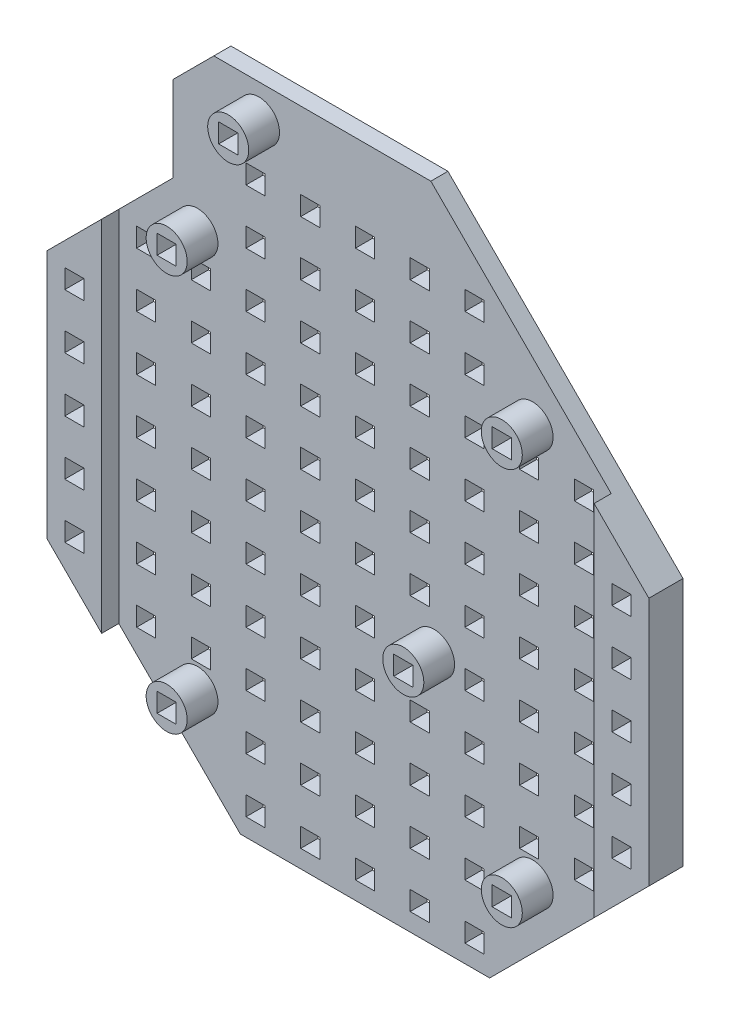
SolidWorks part; units mm, degrees
ref_plane "Plano frontal" through (0, 0, 0) normal (0, 0, 1) x (1, 0, 0)
ref_plane "Plano superior" through (0, 0, 0) normal (0, 1, 0) x (1, 0, 0)
ref_plane "Plano direito" through (0, 0, 0) normal (1, 0, 0) x (0, 0, -1)
sketch "Esboço1" plane through (0, 0, 0) normal (0, 0, 1) x (1, 0, 0)
  line L1 (63.5, -26.3026) -> (63.5, 26.3026)
  line L2 (63.5, 26.3026) -> (26.3026, 63.5)
  line L3 (26.3026, 63.5) -> (-26.3026, 63.5)
  line L4 (-26.3026, 63.5) -> (-63.5, 26.3026)
  line L5 (-63.5, 26.3026) -> (-63.5, -26.3026)
  line L6 (-63.5, -26.3026) -> (-26.3026, -63.5)
  line L7 (-26.3026, -63.5) -> (26.3026, -63.5)
  line L8 (26.3026, -63.5) -> (63.5, -26.3026)
  circle A0 centre (0, 0) radius 63.5 construction
  dimension "D1" = 127
extrude "Ressalto-extrusão1" add sketch "Esboço1" along normal blind 2.5
sketch "Esboço3"
sketch "Esboço2" plane through (0, 0, 0) normal (0, 0, -1) x (-1, 0, 0)
  line L0 (-45, 0) -> (45, 0) construction
  line L1 (-28.75, 0) -> (28.75, 0) construction
  line L2 (28.75, 0) -> (28.75, 8.5) construction
  line L3 (0, 0) -> (0, 75.734) construction
  line L4 (54, 24) -> (36, 24)
  line L5 (57, 21) -> (57, -21)
  line L6 (54, -24) -> (36, -24)
  line L7 (33, 21) -> (33, -21)
  line L8 (57, 24) -> (33, -24) construction
  line L9 (57, -24) -> (33, 24) construction
  line L10 (-57, -24) -> (-33, 24) construction
  line L11 (-57, 24) -> (-33, -24) construction
  line L12 (-28.75, 0) -> (-28.75, 8.5) construction
  line L13 (-33, 21) -> (-33, -21)
  line L14 (-54, -24) -> (-36, -24)
  line L15 (-57, 21) -> (-57, -21)
  line L16 (-54, 24) -> (-36, 24)
  line L17 (0, 0) -> (0, -57) construction
  line L18 (0, -57) -> (-6.731, -57) construction
  circle A0 centre (28.75, 8.5) radius 1.15
  circle A1 centre (28.75, -8.5) radius 1.15
  arc A2 (36, 24) -> (33, 21) centre (36, 21) ccw
  arc A3 (36, -24) -> (33, -21) centre (36, -21) cw
  arc A4 (57, -21) -> (54, -24) centre (54, -21) cw
  arc A5 (54, 24) -> (57, 21) centre (54, 21) cw
  arc A6 (-54, 24) -> (-57, 21) centre (-54, 21) ccw
  arc A7 (-57, -21) -> (-54, -24) centre (-54, -21) ccw
  arc A8 (-36, -24) -> (-33, -21) centre (-36, -21) ccw
  arc A9 (-36, 24) -> (-33, 21) centre (-36, 21) cw
  circle A10 centre (-28.75, -8.5) radius 1.15
  circle A11 centre (-28.75, 8.5) radius 1.15
  circle A12 centre (-6.731, -57) radius 1.15
  circle A13 centre (6.731, -57) radius 1.15
  circle A14 centre (6.731, 57) radius 1.15
  circle A15 centre (-6.731, 57) radius 1.15
  dimension "D6" = 3
  dimension "D8" = 6.731
  dimension "D1" = 45
  dimension "D2" = 48
  dimension "D3" = 24
  dimension "D4" = 28.75
  dimension "D5" = 8.5
  dimension "D7" = 57
sketch "Esboço5" plane through (0, 0, 0) normal (0, 0, 1) x (1, 0, 0)
  line L0 (-44.9013, -44.9013) -> (-42.0729, -42.0729) construction
  line L1 (-47.7297, -34.4361) -> (-49.7096, -36.416)
  line L2 (-42.0729, -40.093) -> (-44.0528, -42.0729)
  line L3 (-42.0729, -40.093) -> (-40.093, -42.0729)
  line L4 (-40.093, -42.0729) -> (-42.0729, -44.0528)
  line L5 (-44.0528, -42.0729) -> (-42.0729, -44.0528)
  line L6 (-42.0729, -40.093) -> (-42.0729, -44.0528) construction
  line L7 (-40.093, -42.0729) -> (-44.0528, -42.0729) construction
  line L8 (-47.7297, -34.4361) -> (-45.7498, -36.416)
  line L9 (-45.7498, -36.416) -> (-47.7297, -38.3959)
  line L10 (-49.7096, -36.416) -> (-47.7297, -38.3959)
  line L11 (-47.7297, -34.4361) -> (-47.7297, -38.3959) construction
  line L12 (-45.7498, -36.416) -> (-49.7096, -36.416) construction
  line L13 (-53.3866, -28.7792) -> (-55.3665, -30.7591)
  line L14 (-53.3866, -28.7792) -> (-51.4067, -30.7591)
  line L15 (-51.4067, -30.7591) -> (-53.3866, -32.739)
  line L16 (-55.3665, -30.7591) -> (-53.3866, -32.739)
  line L17 (-53.3866, -28.7792) -> (-53.3866, -32.739) construction
  line L18 (-51.4067, -30.7591) -> (-55.3665, -30.7591) construction
  line L19 (-60.9, 25.2256) -> (-59.0434, 27.0822)
  line L20 (-57.0635, 25.1023) -> (-59.0434, 27.0822)
  line L21 (-58.1, 6.6) -> (-58.1, 9.4)
  line L22 (-58.1, -1.4) -> (-58.1, 1.4)
  line L23 (-58.1, -1.4) -> (-60.9, -1.4)
  line L24 (-60.9, -1.4) -> (-60.9, 1.4)
  line L25 (-58.1, 1.4) -> (-60.9, 1.4)
  line L26 (-30.7591, -51.4067) -> (-30.7591, -55.3665) construction
  line L27 (-28.7792, -53.3866) -> (-32.739, -53.3866) construction
  line L28 (-36.416, -45.7498) -> (-36.416, -49.7096) construction
  line L29 (-34.4361, -47.7297) -> (-38.3959, -47.7297) construction
  line L30 (-42.0729, -40.093) -> (-42.0729, -44.0528) construction
  line L31 (-40.093, -42.0729) -> (-44.0528, -42.0729) construction
  line L32 (-25.2256, -60.9) -> (-27.0822, -59.0434)
  line L33 (-25.1023, -57.0635) -> (-27.0822, -59.0434)
  line L34 (-58.1, 6.6) -> (-60.9, 6.6)
  line L35 (-30.7591, -55.3665) -> (-32.739, -53.3866)
  line L36 (-30.7591, -51.4067) -> (-32.739, -53.3866)
  line L37 (-28.7792, -53.3866) -> (-30.7591, -51.4067)
  line L38 (-28.7792, -53.3866) -> (-30.7591, -55.3665)
  line L39 (-36.416, -49.7096) -> (-38.3959, -47.7297)
  line L40 (-36.416, -45.7498) -> (-38.3959, -47.7297)
  line L41 (-34.4361, -47.7297) -> (-36.416, -45.7498)
  line L42 (-34.4361, -47.7297) -> (-36.416, -49.7096)
  line L43 (0, -63.5) -> (0, -59.5) construction
  line L44 (-6.6, -58.1) -> (-9.4, -58.1)
  line L45 (1.4, -58.1) -> (-1.4, -58.1)
  line L46 (1.4, -58.1) -> (1.4, -60.9)
  line L47 (1.4, -60.9) -> (-1.4, -60.9)
  line L48 (-1.4, -58.1) -> (-1.4, -60.9)
  line L49 (1.4, -58.1) -> (-1.4, -60.9) construction
  line L50 (1.4, -60.9) -> (-1.4, -58.1) construction
  line L51 (-6.6, -58.1) -> (-6.6, -60.9)
  line L52 (-6.6, -60.9) -> (-9.4, -60.9)
  line L53 (-9.4, -58.1) -> (-9.4, -60.9)
  line L54 (-6.6, -58.1) -> (-9.4, -60.9) construction
  line L55 (-6.6, -60.9) -> (-9.4, -58.1) construction
  line L56 (-14.6, -58.1) -> (-17.4, -58.1)
  line L57 (-14.6, -58.1) -> (-14.6, -60.9)
  line L58 (-14.6, -60.9) -> (-17.4, -60.9)
  line L59 (-17.4, -58.1) -> (-17.4, -60.9)
  line L60 (-14.6, -58.1) -> (-17.4, -60.9) construction
  line L61 (-14.6, -60.9) -> (-17.4, -58.1) construction
  line L62 (-22.6, -58.1) -> (-24.0658, -58.1)
  line L63 (-22.6, -58.1) -> (-22.6, -60.9)
  line L64 (-22.6, -60.9) -> (-25.2256, -60.9)
  line L65 (-60.9, 6.6) -> (-60.9, 9.4)
  line L66 (-58.1, 9.4) -> (-60.9, 9.4)
  line L67 (-58.1, 14.6) -> (-58.1, 17.4)
  line L68 (-58.1, 14.6) -> (-60.9, 14.6)
  line L69 (-60.9, 14.6) -> (-60.9, 17.4)
  line L70 (-58.1, 17.4) -> (-60.9, 17.4)
  line L71 (-17.4, 6.6) -> (-14.6, 6.6)
  line L72 (16, 24) -> (0, 24) construction
  line L73 (0, 24) -> (-16, 24) construction
  line L74 (-24.0658, -58.1) -> (-25.1023, -57.0635)
  line L75 (-58.1, 22.6) -> (-58.1, 24.0658)
  line L76 (-58.1, 22.6) -> (-60.9, 22.6)
  line L77 (-25.4, 46.6) -> (-22.6, 49.4) construction
  line L78 (-60.9, 22.6) -> (-60.9, 25.2256)
  line L79 (-58.1, 24.0658) -> (-57.0635, 25.1023)
  line L80 (-58.1, -24.0658) -> (-57.0635, -25.1023)
  line L81 (-60.9, -22.6) -> (-60.9, -25.2256)
  line L82 (-58.1, -22.6) -> (-60.9, -22.6)
  line L83 (-58.1, -22.6) -> (-58.1, -24.0658)
  line L84 (-58.1, -17.4) -> (-60.9, -17.4)
  line L85 (-60.9, -14.6) -> (-60.9, -17.4)
  line L86 (-58.1, -14.6) -> (-60.9, -14.6)
  line L87 (-58.1, -14.6) -> (-58.1, -17.4)
  line L88 (-58.1, -9.4) -> (-60.9, -9.4)
  line L89 (-60.9, -6.6) -> (-60.9, -9.4)
  line L90 (-58.1, -6.6) -> (-60.9, -6.6)
  line L91 (-58.1, -6.6) -> (-58.1, -9.4)
  line L92 (0, 0) -> (0, 63.5) construction
  line L93 (-25.4, 49.4) -> (-22.6, 46.6) construction
  line L94 (-57.0635, -25.1023) -> (-59.0434, -27.0822)
  line L95 (-60.9, -25.2256) -> (-59.0434, -27.0822)
  line L96 (-63.5, 0) -> (-59.5, 0) construction
  line L97 (-58.1, -1.4) -> (-60.9, 1.4) construction
  line L98 (-60.9, -1.4) -> (-58.1, 1.4) construction
  line L99 (14.6, -60.9) -> (17.4, -58.1) construction
  line L100 (14.6, -58.1) -> (17.4, -60.9) construction
  line L101 (6.6, -60.9) -> (9.4, -58.1) construction
  line L102 (6.6, -58.1) -> (9.4, -60.9) construction
  line L103 (40.093, -42.0729) -> (44.0528, -42.0729) construction
  line L104 (42.0729, -40.093) -> (42.0729, -44.0528) construction
  line L105 (34.4361, -47.7297) -> (38.3959, -47.7297) construction
  line L106 (36.416, -45.7498) -> (36.416, -49.7096) construction
  line L107 (28.7792, -53.3866) -> (32.739, -53.3866) construction
  line L108 (30.7591, -51.4067) -> (30.7591, -55.3665) construction
  line L109 (-58.1, 6.6) -> (-60.9, 9.4) construction
  line L110 (-60.9, 6.6) -> (-58.1, 9.4) construction
  line L111 (-58.1, 14.6) -> (-60.9, 17.4) construction
  line L112 (51.4067, -30.7591) -> (55.3665, -30.7591) construction
  line L113 (53.3866, -28.7792) -> (53.3866, -32.739) construction
  line L114 (45.7498, -36.416) -> (49.7096, -36.416) construction
  line L115 (47.7297, -34.4361) -> (47.7297, -38.3959) construction
  line L116 (40.093, -42.0729) -> (44.0528, -42.0729) construction
  line L117 (42.0729, -40.093) -> (42.0729, -44.0528) construction
  line L118 (44.9013, -44.9013) -> (42.0729, -42.0729) construction
  line L119 (-60.9, 14.6) -> (-58.1, 17.4) construction
  line L120 (-60.9, -14.6) -> (-58.1, -17.4) construction
  line L121 (-58.1, -14.6) -> (-60.9, -17.4) construction
  line L122 (-60.9, -6.6) -> (-58.1, -9.4) construction
  line L123 (-58.1, -6.6) -> (-60.9, -9.4) construction
  line L124 (25.2256, 60.9) -> (27.0822, 59.0434)
  line L125 (25.1023, 57.0635) -> (27.0822, 59.0434)
  line L126 (24.0658, -58.1) -> (25.1023, -57.0635)
  line L127 (6.6, 58.1) -> (9.4, 58.1)
  line L128 (-1.4, 58.1) -> (1.4, 58.1)
  line L129 (-1.4, 58.1) -> (-1.4, 60.9)
  line L130 (-1.4, 60.9) -> (1.4, 60.9)
  line L131 (22.6, -60.9) -> (25.2256, -60.9)
  line L132 (22.6, -58.1) -> (22.6, -60.9)
  line L133 (22.6, -58.1) -> (24.0658, -58.1)
  line L134 (17.4, -58.1) -> (17.4, -60.9)
  line L135 (14.6, -60.9) -> (17.4, -60.9)
  line L136 (14.6, -58.1) -> (14.6, -60.9)
  line L137 (14.6, -58.1) -> (17.4, -58.1)
  line L138 (9.4, -58.1) -> (9.4, -60.9)
  line L139 (6.6, -60.9) -> (9.4, -60.9)
  line L140 (6.6, -58.1) -> (6.6, -60.9)
  line L141 (6.6, -58.1) -> (9.4, -58.1)
  line L142 (34.4361, -47.7297) -> (36.416, -49.7096)
  line L143 (40.093, -42.0729) -> (42.0729, -44.0528)
  line L144 (42.0729, -40.093) -> (44.0528, -42.0729)
  line L145 (34.4361, -47.7297) -> (36.416, -45.7498)
  line L146 (36.416, -45.7498) -> (38.3959, -47.7297)
  line L147 (36.416, -49.7096) -> (38.3959, -47.7297)
  line L148 (28.7792, -53.3866) -> (30.7591, -55.3665)
  line L149 (28.7792, -53.3866) -> (30.7591, -51.4067)
  line L150 (30.7591, -51.4067) -> (32.739, -53.3866)
  line L151 (30.7591, -55.3665) -> (32.739, -53.3866)
  line L152 (1.4, 58.1) -> (1.4, 60.9)
  line L153 (25.1023, -57.0635) -> (27.0822, -59.0434)
  line L154 (25.2256, -60.9) -> (27.0822, -59.0434)
  line L155 (6.6, 58.1) -> (6.6, 60.9)
  line L156 (6.6, 60.9) -> (9.4, 60.9)
  line L157 (9.4, 58.1) -> (9.4, 60.9)
  line L158 (14.6, 58.1) -> (17.4, 58.1)
  line L159 (55.3665, -30.7591) -> (53.3866, -32.739)
  line L160 (51.4067, -30.7591) -> (53.3866, -32.739)
  line L161 (53.3866, -28.7792) -> (51.4067, -30.7591)
  line L162 (53.3866, -28.7792) -> (55.3665, -30.7591)
  line L163 (49.7096, -36.416) -> (47.7297, -38.3959)
  line L164 (45.7498, -36.416) -> (47.7297, -38.3959)
  line L165 (47.7297, -34.4361) -> (45.7498, -36.416)
  line L166 (44.0528, -42.0729) -> (42.0729, -44.0528)
  line L167 (42.0729, -40.093) -> (40.093, -42.0729)
  line L168 (47.7297, -34.4361) -> (49.7096, -36.416)
  line L169 (44.9013, 44.9013) -> (42.0729, 42.0729) construction
  line L170 (42.0729, 40.093) -> (42.0729, 44.0528) construction
  line L171 (40.093, 42.0729) -> (44.0528, 42.0729) construction
  line L172 (47.7297, 34.4361) -> (47.7297, 38.3959) construction
  line L173 (45.7498, 36.416) -> (49.7096, 36.416) construction
  line L174 (53.3866, 28.7792) -> (53.3866, 32.739) construction
  line L175 (51.4067, 30.7591) -> (55.3665, 30.7591) construction
  line L176 (14.6, 58.1) -> (14.6, 60.9)
  line L177 (14.6, 60.9) -> (17.4, 60.9)
  line L178 (30.7591, 51.4067) -> (30.7591, 55.3665) construction
  line L179 (28.7792, 53.3866) -> (32.739, 53.3866) construction
  line L180 (36.416, 45.7498) -> (36.416, 49.7096) construction
  line L181 (34.4361, 47.7297) -> (38.3959, 47.7297) construction
  line L182 (42.0729, 40.093) -> (42.0729, 44.0528) construction
  line L183 (40.093, 42.0729) -> (44.0528, 42.0729) construction
  line L184 (17.4, 58.1) -> (17.4, 60.9)
  line L185 (22.6, 58.1) -> (24.0658, 58.1)
  line L186 (22.6, 58.1) -> (22.6, 60.9)
  line L187 (22.6, 60.9) -> (25.2256, 60.9)
  line L188 (24.0658, 58.1) -> (25.1023, 57.0635)
  line L189 (-24.0658, 58.1) -> (-25.1023, 57.0635)
  line L190 (-22.6, 60.9) -> (-25.2256, 60.9)
  line L191 (-22.6, 58.1) -> (-22.6, 60.9)
  line L192 (-22.6, 58.1) -> (-24.0658, 58.1)
  line L193 (-17.4, 58.1) -> (-17.4, 60.9)
  line L194 (-14.6, 60.9) -> (-17.4, 60.9)
  line L195 (-14.6, 58.1) -> (-14.6, 60.9)
  line L196 (-14.6, 58.1) -> (-17.4, 58.1)
  line L197 (-9.4, 58.1) -> (-9.4, 60.9)
  line L198 (-6.6, 60.9) -> (-9.4, 60.9)
  line L199 (-6.6, 58.1) -> (-6.6, 60.9)
  line L200 (-6.6, 58.1) -> (-9.4, 58.1)
  line L201 (-25.1023, 57.0635) -> (-27.0822, 59.0434)
  line L202 (-25.2256, 60.9) -> (-27.0822, 59.0434)
  line L203 (-40.093, 42.0729) -> (-44.0528, 42.0729) construction
  line L204 (-42.0729, 40.093) -> (-42.0729, 44.0528) construction
  line L205 (-34.4361, 47.7297) -> (-38.3959, 47.7297) construction
  line L206 (-36.416, 45.7498) -> (-36.416, 49.7096) construction
  line L207 (-28.7792, 53.3866) -> (-32.739, 53.3866) construction
  line L208 (-30.7591, 51.4067) -> (-30.7591, 55.3665) construction
  line L209 (0, 63.5) -> (0, 59.5) construction
  line L210 (-1.4, 58.1) -> (1.4, 60.9) construction
  line L211 (-51.4067, 30.7591) -> (-55.3665, 30.7591) construction
  line L212 (-53.3866, 28.7792) -> (-53.3866, 32.739) construction
  line L213 (-45.7498, 36.416) -> (-49.7096, 36.416) construction
  line L214 (-47.7297, 34.4361) -> (-47.7297, 38.3959) construction
  line L215 (-40.093, 42.0729) -> (-44.0528, 42.0729) construction
  line L216 (-42.0729, 40.093) -> (-42.0729, 44.0528) construction
  line L217 (-44.9013, 44.9013) -> (-42.0729, 42.0729) construction
  line L218 (47.7297, 34.4361) -> (49.7096, 36.416)
  line L219 (42.0729, 40.093) -> (44.0528, 42.0729)
  line L220 (42.0729, 40.093) -> (40.093, 42.0729)
  line L221 (40.093, 42.0729) -> (42.0729, 44.0528)
  line L222 (44.0528, 42.0729) -> (42.0729, 44.0528)
  line L223 (47.7297, 34.4361) -> (45.7498, 36.416)
  line L224 (45.7498, 36.416) -> (47.7297, 38.3959)
  line L225 (49.7096, 36.416) -> (47.7297, 38.3959)
  line L226 (53.3866, 28.7792) -> (55.3665, 30.7591)
  line L227 (53.3866, 28.7792) -> (51.4067, 30.7591)
  line L228 (51.4067, 30.7591) -> (53.3866, 32.739)
  line L229 (55.3665, 30.7591) -> (53.3866, 32.739)
  line L230 (-1.4, 60.9) -> (1.4, 58.1) construction
  line L231 (6.6, 58.1) -> (9.4, 60.9) construction
  line L232 (6.6, 60.9) -> (9.4, 58.1) construction
  line L233 (14.6, 58.1) -> (17.4, 60.9) construction
  line L234 (14.6, 60.9) -> (17.4, 58.1) construction
  line L235 (-14.6, 60.9) -> (-17.4, 58.1) construction
  line L236 (-14.6, 58.1) -> (-17.4, 60.9) construction
  line L237 (30.7591, 55.3665) -> (32.739, 53.3866)
  line L238 (30.7591, 51.4067) -> (32.739, 53.3866)
  line L239 (28.7792, 53.3866) -> (30.7591, 51.4067)
  line L240 (28.7792, 53.3866) -> (30.7591, 55.3665)
  line L241 (36.416, 49.7096) -> (38.3959, 47.7297)
  line L242 (36.416, 45.7498) -> (38.3959, 47.7297)
  line L243 (34.4361, 47.7297) -> (36.416, 45.7498)
  line L244 (34.4361, 47.7297) -> (36.416, 49.7096)
  line L245 (-6.6, 60.9) -> (-9.4, 58.1) construction
  line L246 (-6.6, 58.1) -> (-9.4, 60.9) construction
  line L247 (60.9, -25.2256) -> (59.0434, -27.0822)
  line L248 (57.0635, -25.1023) -> (59.0434, -27.0822)
  line L249 (58.1, -6.6) -> (58.1, -9.4)
  line L250 (58.1, 1.4) -> (58.1, -1.4)
  line L251 (58.1, 1.4) -> (60.9, 1.4)
  line L252 (60.9, 1.4) -> (60.9, -1.4)
  line L253 (58.1, -1.4) -> (60.9, -1.4)
  line L254 (58.1, -6.6) -> (60.9, -6.6)
  line L255 (60.9, -6.6) -> (60.9, -9.4)
  line L256 (58.1, -9.4) -> (60.9, -9.4)
  line L257 (58.1, -14.6) -> (58.1, -17.4)
  line L258 (58.1, -14.6) -> (60.9, -14.6)
  line L259 (60.9, -14.6) -> (60.9, -17.4)
  line L260 (58.1, -17.4) -> (60.9, -17.4)
  line L261 (58.1, -22.6) -> (58.1, -24.0658)
  line L262 (58.1, -22.6) -> (60.9, -22.6)
  line L263 (60.9, -22.6) -> (60.9, -25.2256)
  line L264 (58.1, -24.0658) -> (57.0635, -25.1023)
  line L265 (58.1, 24.0658) -> (57.0635, 25.1023)
  line L266 (60.9, 22.6) -> (60.9, 25.2256)
  line L267 (58.1, 22.6) -> (60.9, 22.6)
  line L268 (58.1, 22.6) -> (58.1, 24.0658)
  line L269 (58.1, 17.4) -> (60.9, 17.4)
  line L270 (60.9, 14.6) -> (60.9, 17.4)
  line L271 (58.1, 14.6) -> (60.9, 14.6)
  line L272 (58.1, 14.6) -> (58.1, 17.4)
  line L273 (58.1, 9.4) -> (60.9, 9.4)
  line L274 (60.9, 6.6) -> (60.9, 9.4)
  line L275 (58.1, 6.6) -> (60.9, 6.6)
  line L276 (58.1, 6.6) -> (58.1, 9.4)
  line L277 (57.0635, 25.1023) -> (59.0434, 27.0822)
  line L278 (60.9, 25.2256) -> (59.0434, 27.0822)
  line L279 (63.5, 0) -> (59.5, 0) construction
  line L280 (58.1, 1.4) -> (60.9, -1.4) construction
  line L281 (60.9, 1.4) -> (58.1, -1.4) construction
  line L282 (58.1, -6.6) -> (60.9, -9.4) construction
  line L283 (60.9, -6.6) -> (58.1, -9.4) construction
  line L284 (58.1, -14.6) -> (60.9, -17.4) construction
  line L285 (60.9, -14.6) -> (58.1, -17.4) construction
  line L286 (60.9, 14.6) -> (58.1, 17.4) construction
  line L287 (-34.4361, 47.7297) -> (-36.416, 49.7096)
  line L288 (-40.093, 42.0729) -> (-42.0729, 44.0528)
  line L289 (-42.0729, 40.093) -> (-44.0528, 42.0729)
  line L290 (-34.4361, 47.7297) -> (-36.416, 45.7498)
  line L291 (-36.416, 45.7498) -> (-38.3959, 47.7297)
  line L292 (-36.416, 49.7096) -> (-38.3959, 47.7297)
  line L293 (-28.7792, 53.3866) -> (-30.7591, 55.3665)
  line L294 (-28.7792, 53.3866) -> (-30.7591, 51.4067)
  line L295 (-30.7591, 51.4067) -> (-32.739, 53.3866)
  line L296 (-30.7591, 55.3665) -> (-32.739, 53.3866)
  line L297 (58.1, 14.6) -> (60.9, 17.4) construction
  line L298 (60.9, 6.6) -> (58.1, 9.4) construction
  line L299 (58.1, 6.6) -> (60.9, 9.4) construction
  line L304 (-55.3665, 30.7591) -> (-53.3866, 32.739)
  line L305 (-51.4067, 30.7591) -> (-53.3866, 32.739)
  line L306 (-53.3866, 28.7792) -> (-51.4067, 30.7591)
  line L307 (-53.3866, 28.7792) -> (-55.3665, 30.7591)
  line L308 (-49.7096, 36.416) -> (-47.7297, 38.3959)
  line L309 (-45.7498, 36.416) -> (-47.7297, 38.3959)
  line L310 (-47.7297, 34.4361) -> (-45.7498, 36.416)
  line L311 (-44.0528, 42.0729) -> (-42.0729, 44.0528)
  line L312 (-42.0729, 40.093) -> (-40.093, 42.0729)
  line L313 (-47.7297, 34.4361) -> (-49.7096, 36.416)
  line L314 (-17.4, 46.6) -> (-14.6, 49.4) construction
  line L315 (-14.6, 9.4) -> (-14.6, 6.6)
  line L316 (-17.4, 9.4) -> (-14.6, 9.4)
  line L317 (-17.4, 9.4) -> (-17.4, 6.6)
  line L318 (-17.4, 6.6) -> (-14.6, 9.4) construction
  line L319 (-17.4, 9.4) -> (-14.6, 6.6) construction
  line L320 (-17.4, -1.4) -> (-14.6, -1.4)
  line L321 (-14.6, 1.4) -> (-14.6, -1.4)
  line L322 (-17.4, 1.4) -> (-14.6, 1.4)
  line L323 (-17.4, 1.4) -> (-17.4, -1.4)
  line L324 (-17.4, -1.4) -> (-14.6, 1.4) construction
  line L325 (-17.4, 1.4) -> (-14.6, -1.4) construction
  line L326 (17.4, 1.4) -> (14.6, -1.4) construction
  line L327 (17.4, -1.4) -> (14.6, 1.4) construction
  line L328 (17.4, 1.4) -> (17.4, -1.4)
  line L329 (17.4, 1.4) -> (14.6, 1.4)
  line L330 (14.6, 1.4) -> (14.6, -1.4)
  line L331 (17.4, -1.4) -> (14.6, -1.4)
  line L332 (25.4, 1.4) -> (22.6, -1.4) construction
  line L333 (25.4, -1.4) -> (22.6, 1.4) construction
  line L334 (25.4, 1.4) -> (25.4, -1.4)
  line L335 (25.4, 1.4) -> (22.6, 1.4)
  line L336 (22.6, 1.4) -> (22.6, -1.4)
  line L337 (25.4, -1.4) -> (22.6, -1.4)
  line L346 (0, 0) -> (76.7252, 0) construction
  line L347 (-17.4, -9.4) -> (-14.6, -9.4)
  line L348 (-14.6, -6.6) -> (-14.6, -9.4)
  line L349 (-17.4, -6.6) -> (-14.6, -6.6)
  line L350 (-17.4, -6.6) -> (-17.4, -9.4)
  line L351 (-17.4, -9.4) -> (-14.6, -6.6) construction
  line L352 (-17.4, -6.6) -> (-14.6, -9.4) construction
  line L362 (17.4, 9.4) -> (14.6, 6.6) construction
  line L363 (17.4, 6.6) -> (14.6, 9.4) construction
  line L364 (17.4, 9.4) -> (17.4, 6.6)
  line L365 (17.4, 9.4) -> (14.6, 9.4)
  line L366 (14.6, 9.4) -> (14.6, 6.6)
  line L367 (17.4, 6.6) -> (14.6, 6.6)
  line L368 (25.4, 9.4) -> (22.6, 6.6) construction
  line L369 (25.4, 6.6) -> (22.6, 9.4) construction
  line L370 (25.4, 9.4) -> (25.4, 6.6)
  line L371 (25.4, 9.4) -> (22.6, 9.4)
  line L372 (22.6, 9.4) -> (22.6, 6.6)
  line L373 (25.4, 6.6) -> (22.6, 6.6)
  line L404 (25.4, 17.4) -> (22.6, 14.6) construction
  line L405 (25.4, 14.6) -> (22.6, 17.4) construction
  line L406 (25.4, 17.4) -> (25.4, 14.6)
  line L407 (25.4, 17.4) -> (22.6, 17.4)
  line L408 (22.6, 17.4) -> (22.6, 14.6)
  line L409 (25.4, 14.6) -> (22.6, 14.6)
  line L434 (17.4, 25.4) -> (14.6, 22.6) construction
  line L435 (17.4, 22.6) -> (14.6, 25.4) construction
  line L436 (17.4, 25.4) -> (17.4, 22.6)
  line L437 (17.4, 25.4) -> (14.6, 25.4)
  line L438 (14.6, 25.4) -> (14.6, 22.6)
  line L439 (17.4, 22.6) -> (14.6, 22.6)
  line L440 (25.4, 25.4) -> (22.6, 22.6) construction
  line L441 (25.4, 22.6) -> (22.6, 25.4) construction
  line L442 (25.4, 25.4) -> (25.4, 22.6)
  line L443 (25.4, 25.4) -> (22.6, 25.4)
  line L444 (22.6, 25.4) -> (22.6, 22.6)
  line L445 (25.4, 22.6) -> (22.6, 22.6)
  line L464 (9.4, 33.4) -> (6.6, 30.6) construction
  line L465 (9.4, 30.6) -> (6.6, 33.4) construction
  line L466 (9.4, 33.4) -> (9.4, 30.6)
  line L467 (9.4, 33.4) -> (6.6, 33.4)
  line L468 (6.6, 33.4) -> (6.6, 30.6)
  line L469 (9.4, 30.6) -> (6.6, 30.6)
  line L470 (17.4, 33.4) -> (14.6, 30.6) construction
  line L471 (17.4, 30.6) -> (14.6, 33.4) construction
  line L472 (17.4, 33.4) -> (17.4, 30.6)
  line L473 (17.4, 33.4) -> (14.6, 33.4)
  line L474 (14.6, 33.4) -> (14.6, 30.6)
  line L475 (17.4, 30.6) -> (14.6, 30.6)
  line L476 (25.4, 33.4) -> (22.6, 30.6) construction
  line L477 (25.4, 30.6) -> (22.6, 33.4) construction
  line L478 (25.4, 33.4) -> (25.4, 30.6)
  line L479 (25.4, 33.4) -> (22.6, 33.4)
  line L480 (22.6, 33.4) -> (22.6, 30.6)
  line L481 (25.4, 30.6) -> (22.6, 30.6)
  line L482 (33.4, 33.4) -> (30.6, 30.6) construction
  line L483 (33.4, 30.6) -> (30.6, 33.4) construction
  line L484 (33.4, 33.4) -> (33.4, 30.6)
  line L485 (33.4, 33.4) -> (30.6, 33.4)
  line L486 (30.6, 33.4) -> (30.6, 30.6)
  line L487 (33.4, 30.6) -> (30.6, 30.6)
  line L488 (41.4, 33.4) -> (38.6, 30.6) construction
  line L489 (41.4, 30.6) -> (38.6, 33.4) construction
  line L490 (41.4, 33.4) -> (41.4, 30.6)
  line L491 (41.4, 33.4) -> (38.6, 33.4)
  line L492 (38.6, 33.4) -> (38.6, 30.6)
  line L493 (41.4, 30.6) -> (38.6, 30.6)
  line L500 (9.4, 41.4) -> (6.6, 38.6) construction
  line L501 (9.4, 38.6) -> (6.6, 41.4) construction
  line L502 (9.4, 41.4) -> (9.4, 38.6)
  line L503 (9.4, 41.4) -> (6.6, 41.4)
  line L504 (6.6, 41.4) -> (6.6, 38.6)
  line L505 (9.4, 38.6) -> (6.6, 38.6)
  line L506 (17.4, 41.4) -> (14.6, 38.6) construction
  line L507 (17.4, 38.6) -> (14.6, 41.4) construction
  line L508 (17.4, 41.4) -> (17.4, 38.6)
  line L509 (17.4, 41.4) -> (14.6, 41.4)
  line L510 (14.6, 41.4) -> (14.6, 38.6)
  line L511 (17.4, 38.6) -> (14.6, 38.6)
  line L512 (25.4, 41.4) -> (22.6, 38.6) construction
  line L513 (25.4, 38.6) -> (22.6, 41.4) construction
  line L514 (25.4, 41.4) -> (25.4, 38.6)
  line L515 (25.4, 41.4) -> (22.6, 41.4)
  line L516 (22.6, 41.4) -> (22.6, 38.6)
  line L517 (25.4, 38.6) -> (22.6, 38.6)
  line L518 (33.4, 41.4) -> (30.6, 38.6) construction
  line L519 (33.4, 38.6) -> (30.6, 41.4) construction
  line L520 (33.4, 41.4) -> (33.4, 38.6)
  line L521 (33.4, 41.4) -> (30.6, 41.4)
  line L522 (30.6, 41.4) -> (30.6, 38.6)
  line L523 (33.4, 38.6) -> (30.6, 38.6)
  line L536 (9.4, 49.4) -> (6.6, 46.6) construction
  line L537 (9.4, 46.6) -> (6.6, 49.4) construction
  line L538 (9.4, 49.4) -> (9.4, 46.6)
  line L539 (9.4, 49.4) -> (6.6, 49.4)
  line L540 (6.6, 49.4) -> (6.6, 46.6)
  line L541 (9.4, 46.6) -> (6.6, 46.6)
  line L542 (17.4, 49.4) -> (14.6, 46.6) construction
  line L543 (17.4, 46.6) -> (14.6, 49.4) construction
  line L544 (17.4, 49.4) -> (17.4, 46.6)
  line L545 (17.4, 49.4) -> (14.6, 49.4)
  line L546 (14.6, 49.4) -> (14.6, 46.6)
  line L547 (17.4, 46.6) -> (14.6, 46.6)
  line L548 (25.4, 49.4) -> (22.6, 46.6) construction
  line L549 (25.4, 46.6) -> (22.6, 49.4) construction
  line L550 (25.4, 49.4) -> (25.4, 46.6)
  line L551 (25.4, 49.4) -> (22.6, 49.4)
  line L552 (22.6, 49.4) -> (22.6, 46.6)
  line L553 (25.4, 46.6) -> (22.6, 46.6)
  line L584 (1.4, 25.4) -> (-1.4, 22.6) construction
  line L585 (1.4, 22.6) -> (-1.4, 25.4) construction
  line L586 (1.4, 25.4) -> (1.4, 22.6)
  line L587 (1.4, 25.4) -> (-1.4, 25.4)
  line L588 (-1.4, 25.4) -> (-1.4, 22.6)
  line L589 (1.4, 22.6) -> (-1.4, 22.6)
  line L590 (1.4, 33.4) -> (-1.4, 30.6) construction
  line L591 (1.4, 30.6) -> (-1.4, 33.4) construction
  line L592 (1.4, 33.4) -> (1.4, 30.6)
  line L593 (1.4, 33.4) -> (-1.4, 33.4)
  line L594 (-1.4, 33.4) -> (-1.4, 30.6)
  line L595 (1.4, 30.6) -> (-1.4, 30.6)
  line L596 (1.4, 41.4) -> (-1.4, 38.6) construction
  line L597 (1.4, 38.6) -> (-1.4, 41.4) construction
  line L598 (1.4, 41.4) -> (1.4, 38.6)
  line L599 (1.4, 41.4) -> (-1.4, 41.4)
  line L600 (-1.4, 41.4) -> (-1.4, 38.6)
  line L601 (1.4, 38.6) -> (-1.4, 38.6)
  line L602 (1.4, 49.4) -> (-1.4, 46.6) construction
  line L603 (1.4, 46.6) -> (-1.4, 49.4) construction
  line L604 (1.4, 49.4) -> (1.4, 46.6)
  line L605 (1.4, 49.4) -> (-1.4, 49.4)
  line L606 (-1.4, 49.4) -> (-1.4, 46.6)
  line L607 (1.4, 46.6) -> (-1.4, 46.6)
  line L608 (-17.4, 49.4) -> (-14.6, 46.6) construction
  line L609 (-9.4, 46.6) -> (-6.6, 49.4) construction
  line L610 (-9.4, 49.4) -> (-6.6, 46.6) construction
  line L611 (-33.4, 38.6) -> (-30.6, 41.4) construction
  line L612 (-33.4, 41.4) -> (-30.6, 38.6) construction
  line L613 (-25.4, 38.6) -> (-22.6, 41.4) construction
  line L614 (-25.4, 41.4) -> (-22.6, 38.6) construction
  line L615 (-17.4, 38.6) -> (-14.6, 41.4) construction
  line L616 (-17.4, 41.4) -> (-14.6, 38.6) construction
  line L617 (-9.4, 38.6) -> (-6.6, 41.4) construction
  line L618 (-9.4, 41.4) -> (-6.6, 38.6) construction
  line L623 (-25.4, 46.6) -> (-22.6, 46.6)
  line L624 (-22.6, 49.4) -> (-22.6, 46.6)
  line L625 (-25.4, 49.4) -> (-22.6, 49.4)
  line L626 (-25.4, 49.4) -> (-25.4, 46.6)
  line L627 (-17.4, 46.6) -> (-14.6, 46.6)
  line L628 (-14.6, 49.4) -> (-14.6, 46.6)
  line L629 (-17.4, 49.4) -> (-14.6, 49.4)
  line L630 (-17.4, 49.4) -> (-17.4, 46.6)
  line L631 (-9.4, 46.6) -> (-6.6, 46.6)
  line L632 (-6.6, 49.4) -> (-6.6, 46.6)
  line L633 (-9.4, 49.4) -> (-6.6, 49.4)
  line L634 (-9.4, 49.4) -> (-9.4, 46.6)
  line L635 (-33.4, 38.6) -> (-30.6, 38.6)
  line L636 (-30.6, 41.4) -> (-30.6, 38.6)
  line L637 (-33.4, 41.4) -> (-30.6, 41.4)
  line L638 (-33.4, 41.4) -> (-33.4, 38.6)
  line L639 (-25.4, 38.6) -> (-22.6, 38.6)
  line L640 (-22.6, 41.4) -> (-22.6, 38.6)
  line L641 (-25.4, 41.4) -> (-22.6, 41.4)
  line L642 (-25.4, 41.4) -> (-25.4, 38.6)
  line L643 (-17.4, 38.6) -> (-14.6, 38.6)
  line L644 (-14.6, 41.4) -> (-14.6, 38.6)
  line L645 (-17.4, 41.4) -> (-14.6, 41.4)
  line L646 (-17.4, 41.4) -> (-17.4, 38.6)
  line L647 (-9.4, 38.6) -> (-6.6, 38.6)
  line L648 (-6.6, 41.4) -> (-6.6, 38.6)
  line L649 (-9.4, 41.4) -> (-6.6, 41.4)
  line L650 (-9.4, 41.4) -> (-9.4, 38.6)
  line L653 (-41.4, 30.6) -> (-38.6, 33.4) construction
  line L654 (-41.4, 33.4) -> (-38.6, 30.6) construction
  line L655 (-33.4, 30.6) -> (-30.6, 33.4) construction
  line L656 (-33.4, 33.4) -> (-30.6, 30.6) construction
  line L657 (-25.4, 30.6) -> (-22.6, 33.4) construction
  line L658 (-25.4, 33.4) -> (-22.6, 30.6) construction
  line L659 (-17.4, 30.6) -> (-14.6, 33.4) construction
  line L660 (-17.4, 33.4) -> (-14.6, 30.6) construction
  line L661 (-9.4, 30.6) -> (-6.6, 33.4) construction
  line L662 (-9.4, 33.4) -> (-6.6, 30.6) construction
  line L663 (-25.4, 22.6) -> (-22.6, 25.4) construction
  line L664 (-25.4, 25.4) -> (-22.6, 22.6) construction
  line L665 (-17.4, 22.6) -> (-14.6, 25.4) construction
  line L666 (-17.4, 25.4) -> (-14.6, 22.6) construction
  line L667 (-25.4, 14.6) -> (-22.6, 17.4) construction
  line L668 (-25.4, 17.4) -> (-22.6, 14.6) construction
  line L673 (-25.4, 6.6) -> (-22.6, 9.4) construction
  line L674 (-25.4, 9.4) -> (-22.6, 6.6) construction
  line L679 (-25.4, -1.4) -> (-22.6, 1.4) construction
  line L680 (-25.4, 1.4) -> (-22.6, -1.4) construction
  line L689 (-41.4, 30.6) -> (-38.6, 30.6)
  line L690 (-38.6, 33.4) -> (-38.6, 30.6)
  line L691 (-41.4, 33.4) -> (-38.6, 33.4)
  line L692 (-41.4, 33.4) -> (-41.4, 30.6)
  line L693 (-33.4, 30.6) -> (-30.6, 30.6)
  line L694 (-30.6, 33.4) -> (-30.6, 30.6)
  line L695 (-33.4, 33.4) -> (-30.6, 33.4)
  line L696 (-33.4, 33.4) -> (-33.4, 30.6)
  line L697 (-25.4, 30.6) -> (-22.6, 30.6)
  line L698 (-22.6, 33.4) -> (-22.6, 30.6)
  line L699 (-25.4, 33.4) -> (-22.6, 33.4)
  line L700 (-25.4, 33.4) -> (-25.4, 30.6)
  line L701 (-17.4, 30.6) -> (-14.6, 30.6)
  line L702 (-14.6, 33.4) -> (-14.6, 30.6)
  line L703 (-17.4, 33.4) -> (-14.6, 33.4)
  line L704 (-17.4, 33.4) -> (-17.4, 30.6)
  line L705 (-9.4, 30.6) -> (-6.6, 30.6)
  line L706 (-6.6, 33.4) -> (-6.6, 30.6)
  line L707 (-9.4, 33.4) -> (-6.6, 33.4)
  line L708 (-9.4, 33.4) -> (-9.4, 30.6)
  line L709 (-25.4, 22.6) -> (-22.6, 22.6)
  line L710 (-22.6, 25.4) -> (-22.6, 22.6)
  line L711 (-25.4, 25.4) -> (-22.6, 25.4)
  line L712 (-25.4, 25.4) -> (-25.4, 22.6)
  line L713 (-17.4, 22.6) -> (-14.6, 22.6)
  line L714 (-14.6, 25.4) -> (-14.6, 22.6)
  line L715 (-17.4, 25.4) -> (-14.6, 25.4)
  line L716 (-17.4, 25.4) -> (-17.4, 22.6)
  line L717 (-25.4, 14.6) -> (-22.6, 14.6)
  line L718 (-22.6, 17.4) -> (-22.6, 14.6)
  line L719 (-25.4, 17.4) -> (-22.6, 17.4)
  line L720 (-25.4, 17.4) -> (-25.4, 14.6)
  line L729 (-25.4, 6.6) -> (-22.6, 6.6)
  line L730 (-22.6, 9.4) -> (-22.6, 6.6)
  line L731 (-25.4, 9.4) -> (-22.6, 9.4)
  line L732 (-25.4, 9.4) -> (-25.4, 6.6)
  line L741 (-25.4, -1.4) -> (-22.6, -1.4)
  line L742 (-22.6, 1.4) -> (-22.6, -1.4)
  line L743 (-25.4, 1.4) -> (-22.6, 1.4)
  line L744 (-25.4, 1.4) -> (-25.4, -1.4)
  line L755 (41.4, -30.6) -> (38.6, -33.4) construction
  line L756 (41.4, -33.4) -> (38.6, -30.6) construction
  line L761 (41.4, -30.6) -> (38.6, -30.6)
  line L762 (38.6, -33.4) -> (38.6, -30.6)
  line L763 (41.4, -33.4) -> (38.6, -33.4)
  line L764 (41.4, -33.4) -> (41.4, -30.6)
  line L771 (-41.4, -33.4) -> (-38.6, -30.6) construction
  line L772 (-41.4, -30.6) -> (-38.6, -33.4) construction
  line L773 (-41.4, -33.4) -> (-41.4, -30.6)
  line L774 (-41.4, -33.4) -> (-38.6, -33.4)
  line L775 (-38.6, -33.4) -> (-38.6, -30.6)
  line L776 (-41.4, -30.6) -> (-38.6, -30.6)
  line L781 (-25.4, -9.4) -> (-22.6, -6.6) construction
  line L782 (-25.4, -6.6) -> (-22.6, -9.4) construction
  line L785 (-17.4, -17.4) -> (-14.6, -14.6) construction
  line L786 (-17.4, -14.6) -> (-14.6, -17.4) construction
  line L787 (-25.4, -17.4) -> (-22.6, -14.6) construction
  line L788 (-25.4, -14.6) -> (-22.6, -17.4) construction
  line L789 (-17.4, -25.4) -> (-14.6, -22.6) construction
  line L790 (-17.4, -22.6) -> (-14.6, -25.4) construction
  line L791 (-25.4, -25.4) -> (-22.6, -22.6) construction
  line L792 (-25.4, -22.6) -> (-22.6, -25.4) construction
  line L795 (-17.4, -33.4) -> (-14.6, -30.6) construction
  line L796 (-17.4, -30.6) -> (-14.6, -33.4) construction
  line L797 (-25.4, -33.4) -> (-22.6, -30.6) construction
  line L798 (-25.4, -30.6) -> (-22.6, -33.4) construction
  line L799 (-33.4, -33.4) -> (-30.6, -30.6) construction
  line L800 (-33.4, -30.6) -> (-30.6, -33.4) construction
  line L801 (-9.4, -41.4) -> (-6.6, -38.6) construction
  line L802 (-9.4, -38.6) -> (-6.6, -41.4) construction
  line L803 (-17.4, -41.4) -> (-14.6, -38.6) construction
  line L804 (-17.4, -38.6) -> (-14.6, -41.4) construction
  line L805 (-25.4, -41.4) -> (-22.6, -38.6) construction
  line L806 (-25.4, -38.6) -> (-22.6, -41.4) construction
  line L807 (-33.4, -41.4) -> (-30.6, -38.6) construction
  line L808 (-33.4, -38.6) -> (-30.6, -41.4) construction
  line L809 (-9.4, -49.4) -> (-6.6, -46.6) construction
  line L810 (-9.4, -46.6) -> (-6.6, -49.4) construction
  line L811 (-17.4, -49.4) -> (-14.6, -46.6) construction
  line L812 (1.4, -46.6) -> (-1.4, -49.4) construction
  line L813 (1.4, -49.4) -> (-1.4, -46.6) construction
  line L814 (1.4, -38.6) -> (-1.4, -41.4) construction
  line L815 (1.4, -41.4) -> (-1.4, -38.6) construction
  line L826 (25.4, -46.6) -> (22.6, -49.4) construction
  line L827 (25.4, -49.4) -> (22.6, -46.6) construction
  line L828 (17.4, -46.6) -> (14.6, -49.4) construction
  line L829 (17.4, -49.4) -> (14.6, -46.6) construction
  line L830 (9.4, -46.6) -> (6.6, -49.4) construction
  line L831 (9.4, -49.4) -> (6.6, -46.6) construction
  line L832 (33.4, -38.6) -> (30.6, -41.4) construction
  line L833 (33.4, -41.4) -> (30.6, -38.6) construction
  line L834 (25.4, -38.6) -> (22.6, -41.4) construction
  line L835 (25.4, -41.4) -> (22.6, -38.6) construction
  line L836 (17.4, -38.6) -> (14.6, -41.4) construction
  line L837 (17.4, -41.4) -> (14.6, -38.6) construction
  line L838 (9.4, -38.6) -> (6.6, -41.4) construction
  line L839 (9.4, -41.4) -> (6.6, -38.6) construction
  line L840 (33.4, -30.6) -> (30.6, -33.4) construction
  line L841 (33.4, -33.4) -> (30.6, -30.6) construction
  line L842 (25.4, -30.6) -> (22.6, -33.4) construction
  line L843 (25.4, -33.4) -> (22.6, -30.6) construction
  line L844 (17.4, -30.6) -> (14.6, -33.4) construction
  line L845 (17.4, -33.4) -> (14.6, -30.6) construction
  line L848 (25.4, -22.6) -> (22.6, -25.4) construction
  line L849 (25.4, -25.4) -> (22.6, -22.6) construction
  line L850 (17.4, -22.6) -> (14.6, -25.4) construction
  line L851 (17.4, -25.4) -> (14.6, -22.6) construction
  line L852 (25.4, -14.6) -> (22.6, -17.4) construction
  line L853 (25.4, -17.4) -> (22.6, -14.6) construction
  line L854 (17.4, -14.6) -> (14.6, -17.4) construction
  line L855 (17.4, -17.4) -> (14.6, -14.6) construction
  line L858 (25.4, -6.6) -> (22.6, -9.4) construction
  line L859 (25.4, -9.4) -> (22.6, -6.6) construction
  line L860 (17.4, -6.6) -> (14.6, -9.4) construction
  line L861 (17.4, -9.4) -> (14.6, -6.6) construction
  line L864 (-17.4, -46.6) -> (-14.6, -49.4) construction
  line L865 (-25.4, -49.4) -> (-22.6, -46.6) construction
  line L866 (-25.4, -46.6) -> (-22.6, -49.4) construction
  line L877 (-25.4, -9.4) -> (-25.4, -6.6)
  line L878 (-25.4, -9.4) -> (-22.6, -9.4)
  line L879 (-22.6, -9.4) -> (-22.6, -6.6)
  line L880 (-25.4, -6.6) -> (-22.6, -6.6)
  line L885 (-17.4, -17.4) -> (-17.4, -14.6)
  line L886 (-17.4, -17.4) -> (-14.6, -17.4)
  line L887 (-14.6, -17.4) -> (-14.6, -14.6)
  line L888 (-17.4, -14.6) -> (-14.6, -14.6)
  line L889 (-25.4, -17.4) -> (-25.4, -14.6)
  line L890 (-25.4, -17.4) -> (-22.6, -17.4)
  line L891 (-22.6, -17.4) -> (-22.6, -14.6)
  line L892 (-25.4, -14.6) -> (-22.6, -14.6)
  line L893 (-17.4, -25.4) -> (-17.4, -22.6)
  line L894 (-17.4, -25.4) -> (-14.6, -25.4)
  line L895 (-14.6, -25.4) -> (-14.6, -22.6)
  line L896 (-17.4, -22.6) -> (-14.6, -22.6)
  line L897 (-25.4, -25.4) -> (-25.4, -22.6)
  line L898 (-25.4, -25.4) -> (-22.6, -25.4)
  line L899 (-22.6, -25.4) -> (-22.6, -22.6)
  line L900 (-25.4, -22.6) -> (-22.6, -22.6)
  line L905 (-17.4, -33.4) -> (-17.4, -30.6)
  line L906 (-17.4, -33.4) -> (-14.6, -33.4)
  line L907 (-14.6, -33.4) -> (-14.6, -30.6)
  line L908 (-17.4, -30.6) -> (-14.6, -30.6)
  line L909 (-25.4, -33.4) -> (-25.4, -30.6)
  line L910 (-25.4, -33.4) -> (-22.6, -33.4)
  line L911 (-22.6, -33.4) -> (-22.6, -30.6)
  line L912 (-25.4, -30.6) -> (-22.6, -30.6)
  line L913 (-33.4, -33.4) -> (-33.4, -30.6)
  line L914 (-33.4, -33.4) -> (-30.6, -33.4)
  line L915 (-30.6, -33.4) -> (-30.6, -30.6)
  line L916 (-33.4, -30.6) -> (-30.6, -30.6)
  line L917 (-9.4, -41.4) -> (-9.4, -38.6)
  line L918 (-9.4, -41.4) -> (-6.6, -41.4)
  line L919 (-6.6, -41.4) -> (-6.6, -38.6)
  line L920 (-9.4, -38.6) -> (-6.6, -38.6)
  line L921 (-17.4, -41.4) -> (-17.4, -38.6)
  line L922 (-17.4, -41.4) -> (-14.6, -41.4)
  line L923 (-14.6, -41.4) -> (-14.6, -38.6)
  line L924 (-17.4, -38.6) -> (-14.6, -38.6)
  line L925 (-25.4, -41.4) -> (-25.4, -38.6)
  line L926 (-25.4, -41.4) -> (-22.6, -41.4)
  line L927 (-22.6, -41.4) -> (-22.6, -38.6)
  line L928 (-25.4, -38.6) -> (-22.6, -38.6)
  line L929 (-33.4, -41.4) -> (-33.4, -38.6)
  line L930 (-33.4, -41.4) -> (-30.6, -41.4)
  line L931 (-30.6, -41.4) -> (-30.6, -38.6)
  line L932 (-33.4, -38.6) -> (-30.6, -38.6)
  line L933 (-9.4, -49.4) -> (-9.4, -46.6)
  line L934 (-9.4, -49.4) -> (-6.6, -49.4)
  line L935 (-6.6, -49.4) -> (-6.6, -46.6)
  line L936 (-9.4, -46.6) -> (-6.6, -46.6)
  line L937 (-17.4, -49.4) -> (-17.4, -46.6)
  line L938 (-17.4, -49.4) -> (-14.6, -49.4)
  line L939 (-14.6, -49.4) -> (-14.6, -46.6)
  line L940 (-17.4, -46.6) -> (-14.6, -46.6)
  line L941 (-25.4, -49.4) -> (-25.4, -46.6)
  line L942 (-25.4, -49.4) -> (-22.6, -49.4)
  line L943 (-22.6, -49.4) -> (-22.6, -46.6)
  line L944 (-25.4, -46.6) -> (-22.6, -46.6)
  line L949 (1.4, -46.6) -> (-1.4, -46.6)
  line L950 (-1.4, -49.4) -> (-1.4, -46.6)
  line L951 (1.4, -49.4) -> (-1.4, -49.4)
  line L952 (1.4, -49.4) -> (1.4, -46.6)
  line L953 (1.4, -38.6) -> (-1.4, -38.6)
  line L954 (-1.4, -41.4) -> (-1.4, -38.6)
  line L955 (1.4, -41.4) -> (-1.4, -41.4)
  line L956 (1.4, -41.4) -> (1.4, -38.6)
  line L977 (25.4, -46.6) -> (22.6, -46.6)
  line L978 (22.6, -49.4) -> (22.6, -46.6)
  line L979 (25.4, -49.4) -> (22.6, -49.4)
  line L980 (25.4, -49.4) -> (25.4, -46.6)
  line L981 (17.4, -46.6) -> (14.6, -46.6)
  line L982 (14.6, -49.4) -> (14.6, -46.6)
  line L983 (17.4, -49.4) -> (14.6, -49.4)
  line L984 (17.4, -49.4) -> (17.4, -46.6)
  line L985 (9.4, -46.6) -> (6.6, -46.6)
  line L986 (6.6, -49.4) -> (6.6, -46.6)
  line L987 (9.4, -49.4) -> (6.6, -49.4)
  line L988 (9.4, -49.4) -> (9.4, -46.6)
  line L989 (33.4, -38.6) -> (30.6, -38.6)
  line L990 (30.6, -41.4) -> (30.6, -38.6)
  line L991 (33.4, -41.4) -> (30.6, -41.4)
  line L992 (33.4, -41.4) -> (33.4, -38.6)
  line L993 (25.4, -38.6) -> (22.6, -38.6)
  line L994 (22.6, -41.4) -> (22.6, -38.6)
  line L995 (25.4, -41.4) -> (22.6, -41.4)
  line L996 (25.4, -41.4) -> (25.4, -38.6)
  line L997 (17.4, -38.6) -> (14.6, -38.6)
  line L998 (14.6, -41.4) -> (14.6, -38.6)
  line L999 (17.4, -41.4) -> (14.6, -41.4)
  line L1000 (17.4, -41.4) -> (17.4, -38.6)
  line L1001 (9.4, -38.6) -> (6.6, -38.6)
  line L1002 (6.6, -41.4) -> (6.6, -38.6)
  line L1003 (9.4, -41.4) -> (6.6, -41.4)
  line L1004 (9.4, -41.4) -> (9.4, -38.6)
  line L1005 (33.4, -30.6) -> (30.6, -30.6)
  line L1006 (30.6, -33.4) -> (30.6, -30.6)
  line L1007 (33.4, -33.4) -> (30.6, -33.4)
  line L1008 (33.4, -33.4) -> (33.4, -30.6)
  line L1009 (25.4, -30.6) -> (22.6, -30.6)
  line L1010 (22.6, -33.4) -> (22.6, -30.6)
  line L1011 (25.4, -33.4) -> (22.6, -33.4)
  line L1012 (25.4, -33.4) -> (25.4, -30.6)
  line L1013 (17.4, -30.6) -> (14.6, -30.6)
  line L1014 (14.6, -33.4) -> (14.6, -30.6)
  line L1015 (17.4, -33.4) -> (14.6, -33.4)
  line L1016 (17.4, -33.4) -> (17.4, -30.6)
  line L1021 (25.4, -22.6) -> (22.6, -22.6)
  line L1022 (22.6, -25.4) -> (22.6, -22.6)
  line L1023 (25.4, -25.4) -> (22.6, -25.4)
  line L1024 (25.4, -25.4) -> (25.4, -22.6)
  line L1025 (17.4, -22.6) -> (14.6, -22.6)
  line L1026 (14.6, -25.4) -> (14.6, -22.6)
  line L1027 (17.4, -25.4) -> (14.6, -25.4)
  line L1028 (17.4, -25.4) -> (17.4, -22.6)
  line L1029 (25.4, -14.6) -> (22.6, -14.6)
  line L1030 (22.6, -17.4) -> (22.6, -14.6)
  line L1031 (25.4, -17.4) -> (22.6, -17.4)
  line L1032 (25.4, -17.4) -> (25.4, -14.6)
  line L1033 (17.4, -14.6) -> (14.6, -14.6)
  line L1034 (14.6, -17.4) -> (14.6, -14.6)
  line L1035 (17.4, -17.4) -> (14.6, -17.4)
  line L1036 (17.4, -17.4) -> (17.4, -14.6)
  line L1041 (25.4, -6.6) -> (22.6, -6.6)
  line L1042 (22.6, -9.4) -> (22.6, -6.6)
  line L1043 (25.4, -9.4) -> (22.6, -9.4)
  line L1044 (25.4, -9.4) -> (25.4, -6.6)
  line L1045 (17.4, -6.6) -> (14.6, -6.6)
  line L1046 (14.6, -9.4) -> (14.6, -6.6)
  line L1047 (17.4, -9.4) -> (14.6, -9.4)
  line L1048 (17.4, -9.4) -> (17.4, -6.6)
  point P2 (-42.0729, -42.0729)
  point P8 (-47.7297, -36.416)
  point P13 (-53.3866, -30.7591)
  point P35 (-30.7591, -53.3866)
  point P36 (-36.416, -47.7297)
  point P39 (0, -59.5)
  point P44 (-8, -59.5)
  point P49 (-16, -59.5)
  point P58 (-59.5, 0)
  point P64 (-59.5, 8)
  point P71 (-59.5, 16)
  point P95 (-59.5, -24)
  point P116 (-59.5, -16)
  point P117 (-59.5, -8)
  point P118 (-59.0434, -25.1023)
  point P139 (0, 59.5)
  point P140 (24, -59.5)
  point P141 (16, -59.5)
  point P142 (8, -59.5)
  point P143 (36.416, -47.7297)
  point P144 (30.7591, -53.3866)
  point P145 (25.1023, -59.0434)
  point P147 (53.3866, -30.7591)
  point P148 (47.7297, -36.416)
  point P166 (8, 59.5)
  point P179 (16, 59.5)
  point P202 (-24, 59.5)
  point P203 (-16, 59.5)
  point P204 (-8, 59.5)
  point P205 (-25.1023, 59.0434)
  point P210 (59.5, 0)
  point P227 (59.5, -8)
  point P242 (59.5, -16)
  point P250 (47.7297, 36.416)
  point P251 (53.3866, 30.7591)
  point P254 (30.7591, 53.3866)
  point P255 (36.416, 47.7297)
  point P266 (-36.416, 47.7297)
  point P267 (-30.7591, 53.3866)
  point P270 (-53.3866, 30.7591)
  point P271 (-47.7297, 36.416)
  point P276 (59.5, 24)
  point P277 (59.5, 16)
  point P278 (59.5, 8)
  point P297 (59.0434, 25.1023)
  point P298 (0, 0)
  dimension "D1" = 4
extrude "Corte-extrusão2" cut sketch "Esboço5" along normal through all
sketch "Esboço7" plane through (0, 0, 0) normal (0, 0, -1) x (-1, 0, 0)
  line L0 (0, 0) -> (0, -69.2181) construction
  line L1 (0, 0) -> (-73.0601, 0) construction
  line L2 (-1.4, 24) -> (1.4, 24) construction
  line L3 (-1.4, 22.6) -> (-1.4, 25.4) construction
  line L4 (1.4, 25.4) -> (1.4, 22.6) construction
  line L5 (0, 0) -> (0, 24) construction
  line L6 (32, 24) -> (32, 30.6) construction
  line L7 (-33.4, 9.4) -> (-33.4, 6.6)
  line L8 (0, 24) -> (32, 24) construction
  line L9 (33.4, 30.6) -> (30.6, 30.6) construction
  line L10 (38.6, 25.4) -> (41.4, 25.4)
  line L11 (30.6, 25.4) -> (33.4, 25.4)
  line L12 (30.6, 25.4) -> (30.6, 22.6)
  line L13 (30.6, 22.6) -> (33.4, 22.6)
  line L14 (33.4, 25.4) -> (33.4, 22.6)
  line L15 (30.6, 25.4) -> (33.4, 22.6) construction
  line L16 (30.6, 22.6) -> (33.4, 25.4) construction
  line L17 (38.6, 25.4) -> (38.6, 22.6)
  line L18 (38.6, 22.6) -> (41.4, 22.6)
  line L19 (41.4, 25.4) -> (41.4, 22.6)
  line L20 (38.6, 25.4) -> (41.4, 22.6) construction
  line L21 (38.6, 22.6) -> (41.4, 25.4) construction
  line L22 (46.6, 25.4) -> (49.4, 25.4)
  line L23 (46.6, 25.4) -> (46.6, 22.6)
  line L24 (46.6, 22.6) -> (49.4, 22.6)
  line L25 (49.4, 25.4) -> (49.4, 22.6)
  line L26 (46.6, 25.4) -> (49.4, 22.6) construction
  line L27 (46.6, 22.6) -> (49.4, 25.4) construction
  line L28 (38.6, 17.4) -> (41.4, 17.4)
  line L29 (38.6, 17.4) -> (38.6, 14.6)
  line L30 (38.6, 14.6) -> (41.4, 14.6)
  line L31 (41.4, 17.4) -> (41.4, 14.6)
  line L32 (38.6, 17.4) -> (41.4, 14.6) construction
  line L33 (38.6, 14.6) -> (41.4, 17.4) construction
  line L34 (46.6, 17.4) -> (49.4, 17.4)
  line L35 (46.6, 17.4) -> (46.6, 14.6)
  line L36 (46.6, 14.6) -> (49.4, 14.6)
  line L37 (49.4, 17.4) -> (49.4, 14.6)
  line L38 (46.6, 17.4) -> (49.4, 14.6) construction
  line L39 (46.6, 14.6) -> (49.4, 17.4) construction
  line L40 (38.6, 9.4) -> (41.4, 9.4)
  line L41 (38.6, 9.4) -> (38.6, 6.6)
  line L42 (38.6, 6.6) -> (41.4, 6.6)
  line L43 (41.4, 9.4) -> (41.4, 6.6)
  line L44 (38.6, 9.4) -> (41.4, 6.6) construction
  line L45 (38.6, 6.6) -> (41.4, 9.4) construction
  line L46 (46.6, 9.4) -> (49.4, 9.4)
  line L47 (46.6, 9.4) -> (46.6, 6.6)
  line L48 (46.6, 6.6) -> (49.4, 6.6)
  line L49 (49.4, 9.4) -> (49.4, 6.6)
  line L50 (46.6, 9.4) -> (49.4, 6.6) construction
  line L51 (46.6, 6.6) -> (49.4, 9.4) construction
  line L52 (38.6, 1.4) -> (41.4, 1.4)
  line L53 (38.6, 1.4) -> (38.6, -1.4)
  line L54 (38.6, -1.4) -> (41.4, -1.4)
  line L55 (41.4, 1.4) -> (41.4, -1.4)
  line L56 (38.6, 1.4) -> (41.4, -1.4) construction
  line L57 (38.6, -1.4) -> (41.4, 1.4) construction
  line L58 (46.6, 1.4) -> (49.4, 1.4)
  line L59 (46.6, 1.4) -> (46.6, -1.4)
  line L60 (46.6, -1.4) -> (49.4, -1.4)
  line L61 (49.4, 1.4) -> (49.4, -1.4)
  line L62 (46.6, 1.4) -> (49.4, -1.4) construction
  line L63 (46.6, -1.4) -> (49.4, 1.4) construction
  line L64 (38.6, -6.6) -> (41.4, -6.6)
  line L65 (38.6, -6.6) -> (38.6, -9.4)
  line L66 (38.6, -9.4) -> (41.4, -9.4)
  line L67 (41.4, -6.6) -> (41.4, -9.4)
  line L68 (38.6, -6.6) -> (41.4, -9.4) construction
  line L69 (38.6, -9.4) -> (41.4, -6.6) construction
  line L70 (46.6, -6.6) -> (49.4, -6.6)
  line L71 (46.6, -6.6) -> (46.6, -9.4)
  line L72 (46.6, -9.4) -> (49.4, -9.4)
  line L73 (49.4, -6.6) -> (49.4, -9.4)
  line L74 (46.6, -6.6) -> (49.4, -9.4) construction
  line L75 (46.6, -9.4) -> (49.4, -6.6) construction
  line L76 (38.6, -14.6) -> (41.4, -14.6)
  line L77 (38.6, -14.6) -> (38.6, -17.4)
  line L78 (38.6, -17.4) -> (41.4, -17.4)
  line L79 (41.4, -14.6) -> (41.4, -17.4)
  line L80 (38.6, -14.6) -> (41.4, -17.4) construction
  line L81 (38.6, -17.4) -> (41.4, -14.6) construction
  line L82 (46.6, -14.6) -> (49.4, -14.6)
  line L83 (46.6, -14.6) -> (46.6, -17.4)
  line L84 (46.6, -17.4) -> (49.4, -17.4)
  line L85 (49.4, -14.6) -> (49.4, -17.4)
  line L86 (46.6, -14.6) -> (49.4, -17.4) construction
  line L87 (46.6, -17.4) -> (49.4, -14.6) construction
  line L88 (38.6, -22.6) -> (41.4, -22.6)
  line L89 (38.6, -22.6) -> (38.6, -25.4)
  line L90 (38.6, -25.4) -> (41.4, -25.4)
  line L91 (41.4, -22.6) -> (41.4, -25.4)
  line L92 (38.6, -22.6) -> (41.4, -25.4) construction
  line L93 (38.6, -25.4) -> (41.4, -22.6) construction
  line L94 (46.6, -22.6) -> (49.4, -22.6)
  line L95 (46.6, -22.6) -> (46.6, -25.4)
  line L96 (46.6, -25.4) -> (49.4, -25.4)
  line L97 (49.4, -22.6) -> (49.4, -25.4)
  line L98 (46.6, -22.6) -> (49.4, -25.4) construction
  line L99 (46.6, -25.4) -> (49.4, -22.6) construction
  line L100 (30.6, 17.4) -> (33.4, 17.4)
  line L101 (30.6, 17.4) -> (30.6, 14.6)
  line L102 (30.6, 14.6) -> (33.4, 14.6)
  line L103 (33.4, 17.4) -> (33.4, 14.6)
  line L104 (30.6, 17.4) -> (33.4, 14.6) construction
  line L105 (30.6, 14.6) -> (33.4, 17.4) construction
  line L106 (30.6, 9.4) -> (33.4, 9.4)
  line L107 (30.6, 9.4) -> (30.6, 6.6)
  line L108 (30.6, 6.6) -> (33.4, 6.6)
  line L109 (33.4, 9.4) -> (33.4, 6.6)
  line L110 (30.6, 9.4) -> (33.4, 6.6) construction
  line L111 (30.6, 6.6) -> (33.4, 9.4) construction
  line L112 (30.6, 1.4) -> (33.4, 1.4)
  line L113 (30.6, 1.4) -> (30.6, -1.4)
  line L114 (30.6, -1.4) -> (33.4, -1.4)
  line L115 (33.4, 1.4) -> (33.4, -1.4)
  line L116 (30.6, 1.4) -> (33.4, -1.4) construction
  line L117 (30.6, -1.4) -> (33.4, 1.4) construction
  line L118 (30.6, -6.6) -> (33.4, -6.6)
  line L119 (30.6, -6.6) -> (30.6, -9.4)
  line L120 (30.6, -9.4) -> (33.4, -9.4)
  line L121 (33.4, -6.6) -> (33.4, -9.4)
  line L122 (30.6, -6.6) -> (33.4, -9.4) construction
  line L123 (30.6, -9.4) -> (33.4, -6.6) construction
  line L124 (30.6, -14.6) -> (33.4, -14.6)
  line L125 (30.6, -14.6) -> (30.6, -17.4)
  line L126 (30.6, -17.4) -> (33.4, -17.4)
  line L127 (33.4, -14.6) -> (33.4, -17.4)
  line L128 (30.6, -14.6) -> (33.4, -17.4) construction
  line L129 (30.6, -17.4) -> (33.4, -14.6) construction
  line L130 (30.6, -22.6) -> (33.4, -22.6)
  line L131 (30.6, -22.6) -> (30.6, -25.4)
  line L132 (30.6, -25.4) -> (33.4, -25.4)
  line L133 (33.4, -22.6) -> (33.4, -25.4)
  line L134 (30.6, -22.6) -> (33.4, -25.4) construction
  line L135 (30.6, -25.4) -> (33.4, -22.6) construction
  line L136 (-30.6, -25.4) -> (-33.4, -22.6) construction
  line L137 (-30.6, -22.6) -> (-33.4, -25.4) construction
  line L138 (-30.6, -17.4) -> (-33.4, -14.6) construction
  line L139 (-30.6, -14.6) -> (-33.4, -17.4) construction
  line L140 (-30.6, 6.6) -> (-33.4, 6.6)
  line L141 (-30.6, 9.4) -> (-30.6, 6.6)
  line L142 (-30.6, 9.4) -> (-33.4, 9.4)
  line L143 (-30.6, 6.6) -> (-33.4, 9.4) construction
  line L144 (-30.6, 9.4) -> (-33.4, 6.6) construction
  line L145 (-33.4, 1.4) -> (-33.4, -1.4)
  line L146 (-30.6, 14.6) -> (-33.4, 17.4) construction
  line L147 (-30.6, 17.4) -> (-33.4, 14.6) construction
  line L148 (-46.6, -25.4) -> (-49.4, -22.6) construction
  line L149 (-46.6, -22.6) -> (-49.4, -25.4) construction
  line L150 (-38.6, -25.4) -> (-41.4, -22.6) construction
  line L151 (-38.6, -22.6) -> (-41.4, -25.4) construction
  line L152 (-46.6, -17.4) -> (-49.4, -14.6) construction
  line L153 (-46.6, -14.6) -> (-49.4, -17.4) construction
  line L154 (-38.6, -17.4) -> (-41.4, -14.6) construction
  line L155 (-38.6, -14.6) -> (-41.4, -17.4) construction
  line L156 (-46.6, -9.4) -> (-49.4, -6.6) construction
  line L157 (-46.6, -6.6) -> (-49.4, -9.4) construction
  line L158 (-38.6, -9.4) -> (-41.4, -6.6) construction
  line L159 (-38.6, -6.6) -> (-41.4, -9.4) construction
  line L160 (-46.6, -1.4) -> (-49.4, 1.4) construction
  line L161 (-46.6, 1.4) -> (-49.4, -1.4) construction
  line L162 (-38.6, -1.4) -> (-41.4, 1.4) construction
  line L163 (-38.6, 1.4) -> (-41.4, -1.4) construction
  line L164 (-46.6, 6.6) -> (-49.4, 9.4) construction
  line L165 (-46.6, 9.4) -> (-49.4, 6.6) construction
  line L166 (-38.6, 6.6) -> (-41.4, 9.4) construction
  line L167 (-38.6, 9.4) -> (-41.4, 6.6) construction
  line L168 (-46.6, 14.6) -> (-49.4, 17.4) construction
  line L169 (-46.6, 17.4) -> (-49.4, 14.6) construction
  line L170 (-38.6, 14.6) -> (-41.4, 17.4) construction
  line L171 (-38.6, 17.4) -> (-41.4, 14.6) construction
  line L172 (-46.6, 22.6) -> (-49.4, 25.4) construction
  line L173 (-46.6, 25.4) -> (-49.4, 22.6) construction
  line L174 (-38.6, 22.6) -> (-41.4, 25.4) construction
  line L175 (-38.6, 25.4) -> (-41.4, 22.6) construction
  line L176 (-30.6, 22.6) -> (-33.4, 25.4) construction
  line L177 (-30.6, 25.4) -> (-33.4, 22.6) construction
  line L178 (-32, 24) -> (-32, 30.6) construction
  line L179 (-33.4, -22.6) -> (-33.4, -25.4)
  line L180 (-30.6, -25.4) -> (-33.4, -25.4)
  line L181 (-30.6, -22.6) -> (-30.6, -25.4)
  line L182 (-30.6, -22.6) -> (-33.4, -22.6)
  line L183 (-33.4, -14.6) -> (-33.4, -17.4)
  line L184 (-30.6, -17.4) -> (-33.4, -17.4)
  line L185 (-30.6, -14.6) -> (-30.6, -17.4)
  line L186 (-30.6, -14.6) -> (-33.4, -14.6)
  line L187 (-30.6, -1.4) -> (-33.4, -1.4)
  line L188 (-30.6, 1.4) -> (-30.6, -1.4)
  line L189 (-30.6, 1.4) -> (-33.4, 1.4)
  line L190 (-30.6, -1.4) -> (-33.4, 1.4) construction
  line L191 (-30.6, 1.4) -> (-33.4, -1.4) construction
  line L192 (-33.4, -6.6) -> (-33.4, -9.4)
  line L193 (-30.6, -9.4) -> (-33.4, -9.4)
  line L194 (-30.6, -6.6) -> (-30.6, -9.4)
  line L195 (-30.6, -6.6) -> (-33.4, -6.6)
  line L196 (-30.6, -9.4) -> (-33.4, -6.6) construction
  line L197 (-30.6, -6.6) -> (-33.4, -9.4) construction
  line L199 (-33.4, 17.4) -> (-33.4, 14.6)
  line L200 (-30.6, 14.6) -> (-33.4, 14.6)
  line L201 (-30.6, 17.4) -> (-30.6, 14.6)
  line L202 (-30.6, 17.4) -> (-33.4, 17.4)
  line L203 (-49.4, -22.6) -> (-49.4, -25.4)
  line L204 (-46.6, -25.4) -> (-49.4, -25.4)
  line L205 (-46.6, -22.6) -> (-46.6, -25.4)
  line L206 (-46.6, -22.6) -> (-49.4, -22.6)
  line L207 (-41.4, -22.6) -> (-41.4, -25.4)
  line L208 (-38.6, -25.4) -> (-41.4, -25.4)
  line L209 (-38.6, -22.6) -> (-38.6, -25.4)
  line L210 (-38.6, -22.6) -> (-41.4, -22.6)
  line L211 (-49.4, -14.6) -> (-49.4, -17.4)
  line L212 (-46.6, -17.4) -> (-49.4, -17.4)
  line L213 (-46.6, -14.6) -> (-46.6, -17.4)
  line L214 (-46.6, -14.6) -> (-49.4, -14.6)
  line L215 (-41.4, -14.6) -> (-41.4, -17.4)
  line L216 (-38.6, -17.4) -> (-41.4, -17.4)
  line L217 (-38.6, -14.6) -> (-38.6, -17.4)
  line L218 (-38.6, -14.6) -> (-41.4, -14.6)
  line L219 (-49.4, -6.6) -> (-49.4, -9.4)
  line L220 (-46.6, -9.4) -> (-49.4, -9.4)
  line L221 (-46.6, -6.6) -> (-46.6, -9.4)
  line L222 (-46.6, -6.6) -> (-49.4, -6.6)
  line L223 (-41.4, -6.6) -> (-41.4, -9.4)
  line L224 (-38.6, -9.4) -> (-41.4, -9.4)
  line L225 (-38.6, -6.6) -> (-38.6, -9.4)
  line L226 (-38.6, -6.6) -> (-41.4, -6.6)
  line L227 (-49.4, 1.4) -> (-49.4, -1.4)
  line L228 (-46.6, -1.4) -> (-49.4, -1.4)
  line L229 (-46.6, 1.4) -> (-46.6, -1.4)
  line L230 (-46.6, 1.4) -> (-49.4, 1.4)
  line L231 (-41.4, 1.4) -> (-41.4, -1.4)
  line L232 (-38.6, -1.4) -> (-41.4, -1.4)
  line L233 (-38.6, 1.4) -> (-38.6, -1.4)
  line L234 (-38.6, 1.4) -> (-41.4, 1.4)
  line L235 (-49.4, 9.4) -> (-49.4, 6.6)
  line L236 (-46.6, 6.6) -> (-49.4, 6.6)
  line L237 (-46.6, 9.4) -> (-46.6, 6.6)
  line L238 (-46.6, 9.4) -> (-49.4, 9.4)
  line L239 (-41.4, 9.4) -> (-41.4, 6.6)
  line L240 (-38.6, 6.6) -> (-41.4, 6.6)
  line L241 (-38.6, 9.4) -> (-38.6, 6.6)
  line L242 (-38.6, 9.4) -> (-41.4, 9.4)
  line L243 (-49.4, 17.4) -> (-49.4, 14.6)
  line L244 (-46.6, 14.6) -> (-49.4, 14.6)
  line L245 (-46.6, 17.4) -> (-46.6, 14.6)
  line L246 (-46.6, 17.4) -> (-49.4, 17.4)
  line L247 (-41.4, 17.4) -> (-41.4, 14.6)
  line L248 (-38.6, 14.6) -> (-41.4, 14.6)
  line L249 (-38.6, 17.4) -> (-38.6, 14.6)
  line L250 (-38.6, 17.4) -> (-41.4, 17.4)
  line L251 (-49.4, 25.4) -> (-49.4, 22.6)
  line L252 (-46.6, 22.6) -> (-49.4, 22.6)
  line L253 (-46.6, 25.4) -> (-46.6, 22.6)
  line L254 (-46.6, 25.4) -> (-49.4, 25.4)
  line L255 (-41.4, 25.4) -> (-41.4, 22.6)
  line L256 (-38.6, 22.6) -> (-41.4, 22.6)
  line L257 (-38.6, 25.4) -> (-38.6, 22.6)
  line L258 (-33.4, 25.4) -> (-33.4, 22.6)
  line L259 (-30.6, 22.6) -> (-33.4, 22.6)
  line L260 (-30.6, 25.4) -> (-30.6, 22.6)
  line L261 (-30.6, 25.4) -> (-33.4, 25.4)
  line L262 (-38.6, 25.4) -> (-41.4, 25.4)
  dimension "D1" = 2.8
  dimension "D2" = 3
  dimension "D3" = 7
  dimension "D4" = 4
extrude "Corte-extrusão3" cut sketch "Esboço7" against normal through all
sketch "Esboço16" plane through (0, 0, 2.5) normal (0, 0, 1) x (1, 0, 0)
  line L0 (-44.9013, -44.9013) -> (-42.0729, -42.0729) construction
  line L1 (-47.7297, -34.4361) -> (-49.7096, -36.416)
  line L2 (-42.0729, -40.093) -> (-44.0528, -42.0729)
  line L3 (-42.0729, -40.093) -> (-40.093, -42.0729)
  line L4 (-40.093, -42.0729) -> (-42.0729, -44.0528)
  line L5 (-44.0528, -42.0729) -> (-42.0729, -44.0528)
  line L6 (-42.0729, -40.093) -> (-42.0729, -44.0528) construction
  line L7 (-40.093, -42.0729) -> (-44.0528, -42.0729) construction
  line L8 (-47.7297, -34.4361) -> (-45.7498, -36.416)
  line L9 (-45.7498, -36.416) -> (-47.7297, -38.3959)
  line L10 (-49.7096, -36.416) -> (-47.7297, -38.3959)
  line L11 (-47.7297, -34.4361) -> (-47.7297, -38.3959) construction
  line L12 (-45.7498, -36.416) -> (-49.7096, -36.416) construction
  line L13 (-53.3866, -28.7792) -> (-55.3665, -30.7591)
  line L14 (-53.3866, -28.7792) -> (-51.4067, -30.7591)
  line L15 (-51.4067, -30.7591) -> (-53.3866, -32.739)
  line L16 (-55.3665, -30.7591) -> (-53.3866, -32.739)
  line L17 (-53.3866, -28.7792) -> (-53.3866, -32.739) construction
  line L18 (-51.4067, -30.7591) -> (-55.3665, -30.7591) construction
  line L19 (-60.9, 25.2256) -> (-59.0434, 27.0822)
  line L20 (-57.0635, 25.1023) -> (-59.0434, 27.0822)
  line L21 (-58.1, 6.6) -> (-58.1, 9.4)
  line L22 (-58.1, -1.4) -> (-58.1, 1.4)
  line L23 (-58.1, -1.4) -> (-60.9, -1.4)
  line L24 (-60.9, -1.4) -> (-60.9, 1.4)
  line L25 (-58.1, 1.4) -> (-60.9, 1.4)
  line L26 (-30.7591, -51.4067) -> (-30.7591, -55.3665) construction
  line L27 (-28.7792, -53.3866) -> (-32.739, -53.3866) construction
  line L28 (-36.416, -45.7498) -> (-36.416, -49.7096) construction
  line L29 (-34.4361, -47.7297) -> (-38.3959, -47.7297) construction
  line L30 (-42.0729, -40.093) -> (-42.0729, -44.0528) construction
  line L31 (-40.093, -42.0729) -> (-44.0528, -42.0729) construction
  line L32 (-25.2256, -60.9) -> (-27.0822, -59.0434)
  line L33 (-25.1023, -57.0635) -> (-27.0822, -59.0434)
  line L34 (-58.1, 6.6) -> (-60.9, 6.6)
  line L35 (-30.7591, -55.3665) -> (-32.739, -53.3866)
  line L36 (-30.7591, -51.4067) -> (-32.739, -53.3866)
  line L37 (-28.7792, -53.3866) -> (-30.7591, -51.4067)
  line L38 (-28.7792, -53.3866) -> (-30.7591, -55.3665)
  line L39 (-36.416, -49.7096) -> (-38.3959, -47.7297)
  line L40 (-36.416, -45.7498) -> (-38.3959, -47.7297)
  line L41 (-34.4361, -47.7297) -> (-36.416, -45.7498)
  line L42 (-34.4361, -47.7297) -> (-36.416, -49.7096)
  line L43 (0, -63.5) -> (0, -59.5) construction
  line L44 (-6.6, -58.1) -> (-9.4, -58.1)
  line L45 (1.4, -58.1) -> (-1.4, -58.1)
  line L46 (1.4, -58.1) -> (1.4, -60.9)
  line L47 (1.4, -60.9) -> (-1.4, -60.9)
  line L48 (-1.4, -58.1) -> (-1.4, -60.9)
  line L49 (1.4, -58.1) -> (-1.4, -60.9) construction
  line L50 (1.4, -60.9) -> (-1.4, -58.1) construction
  line L51 (-6.6, -58.1) -> (-6.6, -60.9)
  line L52 (-6.6, -60.9) -> (-9.4, -60.9)
  line L53 (-9.4, -58.1) -> (-9.4, -60.9)
  line L54 (-6.6, -58.1) -> (-9.4, -60.9) construction
  line L55 (-6.6, -60.9) -> (-9.4, -58.1) construction
  line L56 (-14.6, -58.1) -> (-17.4, -58.1)
  line L57 (-14.6, -58.1) -> (-14.6, -60.9)
  line L58 (-14.6, -60.9) -> (-17.4, -60.9)
  line L59 (-17.4, -58.1) -> (-17.4, -60.9)
  line L60 (-14.6, -58.1) -> (-17.4, -60.9) construction
  line L61 (-14.6, -60.9) -> (-17.4, -58.1) construction
  line L62 (-22.6, -58.1) -> (-24.0658, -58.1)
  line L63 (-22.6, -58.1) -> (-22.6, -60.9)
  line L64 (-22.6, -60.9) -> (-25.2256, -60.9)
  line L65 (-60.9, 6.6) -> (-60.9, 9.4)
  line L66 (-58.1, 9.4) -> (-60.9, 9.4)
  line L67 (-58.1, 14.6) -> (-58.1, 17.4)
  line L68 (-58.1, 14.6) -> (-60.9, 14.6)
  line L69 (-60.9, 14.6) -> (-60.9, 17.4)
  line L70 (-58.1, 17.4) -> (-60.9, 17.4)
  line L72 (-26.3026, -63.5) -> (26.3026, -63.5)
  line L73 (26.3026, -63.5) -> (63.5, -26.3026)
  line L74 (-24.0658, -58.1) -> (-25.1023, -57.0635)
  line L75 (-58.1, 22.6) -> (-58.1, 24.0658)
  line L76 (-58.1, 22.6) -> (-60.9, 22.6)
  line L77 (63.5, -26.3026) -> (63.5, 26.3026)
  line L78 (-60.9, 22.6) -> (-60.9, 25.2256)
  line L79 (-58.1, 24.0658) -> (-57.0635, 25.1023)
  line L80 (-58.1, -24.0658) -> (-57.0635, -25.1023)
  line L81 (-60.9, -22.6) -> (-60.9, -25.2256)
  line L82 (-58.1, -22.6) -> (-60.9, -22.6)
  line L83 (-58.1, -22.6) -> (-58.1, -24.0658)
  line L84 (-58.1, -17.4) -> (-60.9, -17.4)
  line L85 (-60.9, -14.6) -> (-60.9, -17.4)
  line L86 (-58.1, -14.6) -> (-60.9, -14.6)
  line L87 (-58.1, -14.6) -> (-58.1, -17.4)
  line L88 (-58.1, -9.4) -> (-60.9, -9.4)
  line L89 (-60.9, -6.6) -> (-60.9, -9.4)
  line L90 (-58.1, -6.6) -> (-60.9, -6.6)
  line L91 (-58.1, -6.6) -> (-58.1, -9.4)
  line L92 (63.5, 26.3026) -> (26.3026, 63.5)
  line L93 (26.3026, 63.5) -> (-26.3026, 63.5)
  line L94 (-57.0635, -25.1023) -> (-59.0434, -27.0822)
  line L95 (-60.9, -25.2256) -> (-59.0434, -27.0822)
  line L96 (-63.5, 0) -> (-59.5, 0) construction
  line L97 (-58.1, -1.4) -> (-60.9, 1.4) construction
  line L98 (-60.9, -1.4) -> (-58.1, 1.4) construction
  line L99 (14.6, -60.9) -> (17.4, -58.1) construction
  line L100 (14.6, -58.1) -> (17.4, -60.9) construction
  line L101 (6.6, -60.9) -> (9.4, -58.1) construction
  line L102 (6.6, -58.1) -> (9.4, -60.9) construction
  line L103 (40.093, -42.0729) -> (44.0528, -42.0729) construction
  line L104 (42.0729, -40.093) -> (42.0729, -44.0528) construction
  line L105 (34.4361, -47.7297) -> (38.3959, -47.7297) construction
  line L106 (36.416, -45.7498) -> (36.416, -49.7096) construction
  line L107 (28.7792, -53.3866) -> (32.739, -53.3866) construction
  line L108 (30.7591, -51.4067) -> (30.7591, -55.3665) construction
  line L109 (-58.1, 6.6) -> (-60.9, 9.4) construction
  line L110 (-60.9, 6.6) -> (-58.1, 9.4) construction
  line L111 (-58.1, 14.6) -> (-60.9, 17.4) construction
  line L112 (51.4067, -30.7591) -> (55.3665, -30.7591) construction
  line L113 (53.3866, -28.7792) -> (53.3866, -32.739) construction
  line L114 (45.7498, -36.416) -> (49.7096, -36.416) construction
  line L115 (47.7297, -34.4361) -> (47.7297, -38.3959) construction
  line L116 (40.093, -42.0729) -> (44.0528, -42.0729) construction
  line L117 (42.0729, -40.093) -> (42.0729, -44.0528) construction
  line L118 (44.9013, -44.9013) -> (42.0729, -42.0729) construction
  line L119 (-60.9, 14.6) -> (-58.1, 17.4) construction
  line L120 (-60.9, -14.6) -> (-58.1, -17.4) construction
  line L121 (-58.1, -14.6) -> (-60.9, -17.4) construction
  line L122 (-60.9, -6.6) -> (-58.1, -9.4) construction
  line L123 (-58.1, -6.6) -> (-60.9, -9.4) construction
  line L124 (25.2256, 60.9) -> (27.0822, 59.0434)
  line L125 (25.1023, 57.0635) -> (27.0822, 59.0434)
  line L126 (24.0658, -58.1) -> (25.1023, -57.0635)
  line L127 (6.6, 58.1) -> (9.4, 58.1)
  line L128 (-1.4, 58.1) -> (1.4, 58.1)
  line L129 (-1.4, 58.1) -> (-1.4, 60.9)
  line L130 (-1.4, 60.9) -> (1.4, 60.9)
  line L131 (22.6, -60.9) -> (25.2256, -60.9)
  line L132 (22.6, -58.1) -> (22.6, -60.9)
  line L133 (22.6, -58.1) -> (24.0658, -58.1)
  line L134 (17.4, -58.1) -> (17.4, -60.9)
  line L135 (14.6, -60.9) -> (17.4, -60.9)
  line L136 (14.6, -58.1) -> (14.6, -60.9)
  line L137 (14.6, -58.1) -> (17.4, -58.1)
  line L138 (9.4, -58.1) -> (9.4, -60.9)
  line L139 (6.6, -60.9) -> (9.4, -60.9)
  line L140 (6.6, -58.1) -> (6.6, -60.9)
  line L141 (6.6, -58.1) -> (9.4, -58.1)
  line L142 (34.4361, -47.7297) -> (36.416, -49.7096)
  line L143 (40.093, -42.0729) -> (42.0729, -44.0528)
  line L144 (42.0729, -40.093) -> (44.0528, -42.0729)
  line L145 (34.4361, -47.7297) -> (36.416, -45.7498)
  line L146 (36.416, -45.7498) -> (38.3959, -47.7297)
  line L147 (36.416, -49.7096) -> (38.3959, -47.7297)
  line L148 (28.7792, -53.3866) -> (30.7591, -55.3665)
  line L149 (28.7792, -53.3866) -> (30.7591, -51.4067)
  line L150 (30.7591, -51.4067) -> (32.739, -53.3866)
  line L151 (30.7591, -55.3665) -> (32.739, -53.3866)
  line L152 (1.4, 58.1) -> (1.4, 60.9)
  line L153 (25.1023, -57.0635) -> (27.0822, -59.0434)
  line L154 (25.2256, -60.9) -> (27.0822, -59.0434)
  line L155 (6.6, 58.1) -> (6.6, 60.9)
  line L156 (6.6, 60.9) -> (9.4, 60.9)
  line L157 (9.4, 58.1) -> (9.4, 60.9)
  line L158 (14.6, 58.1) -> (17.4, 58.1)
  line L159 (55.3665, -30.7591) -> (53.3866, -32.739)
  line L160 (51.4067, -30.7591) -> (53.3866, -32.739)
  line L161 (53.3866, -28.7792) -> (51.4067, -30.7591)
  line L162 (53.3866, -28.7792) -> (55.3665, -30.7591)
  line L163 (49.7096, -36.416) -> (47.7297, -38.3959)
  line L164 (45.7498, -36.416) -> (47.7297, -38.3959)
  line L165 (47.7297, -34.4361) -> (45.7498, -36.416)
  line L166 (44.0528, -42.0729) -> (42.0729, -44.0528)
  line L167 (42.0729, -40.093) -> (40.093, -42.0729)
  line L168 (47.7297, -34.4361) -> (49.7096, -36.416)
  line L169 (44.9013, 44.9013) -> (42.0729, 42.0729) construction
  line L170 (42.0729, 40.093) -> (42.0729, 44.0528) construction
  line L171 (40.093, 42.0729) -> (44.0528, 42.0729) construction
  line L172 (47.7297, 34.4361) -> (47.7297, 38.3959) construction
  line L173 (45.7498, 36.416) -> (49.7096, 36.416) construction
  line L174 (53.3866, 28.7792) -> (53.3866, 32.739) construction
  line L175 (51.4067, 30.7591) -> (55.3665, 30.7591) construction
  line L176 (14.6, 58.1) -> (14.6, 60.9)
  line L177 (14.6, 60.9) -> (17.4, 60.9)
  line L178 (30.7591, 51.4067) -> (30.7591, 55.3665) construction
  line L179 (28.7792, 53.3866) -> (32.739, 53.3866) construction
  line L180 (36.416, 45.7498) -> (36.416, 49.7096) construction
  line L181 (34.4361, 47.7297) -> (38.3959, 47.7297) construction
  line L182 (42.0729, 40.093) -> (42.0729, 44.0528) construction
  line L183 (40.093, 42.0729) -> (44.0528, 42.0729) construction
  line L184 (17.4, 58.1) -> (17.4, 60.9)
  line L185 (22.6, 58.1) -> (24.0658, 58.1)
  line L186 (22.6, 58.1) -> (22.6, 60.9)
  line L187 (22.6, 60.9) -> (25.2256, 60.9)
  line L188 (24.0658, 58.1) -> (25.1023, 57.0635)
  line L189 (-24.0658, 58.1) -> (-25.1023, 57.0635)
  line L190 (-22.6, 60.9) -> (-25.2256, 60.9)
  line L191 (-22.6, 58.1) -> (-22.6, 60.9)
  line L192 (-22.6, 58.1) -> (-24.0658, 58.1)
  line L193 (-17.4, 58.1) -> (-17.4, 60.9)
  line L194 (-14.6, 60.9) -> (-17.4, 60.9)
  line L195 (-14.6, 58.1) -> (-14.6, 60.9)
  line L196 (-14.6, 58.1) -> (-17.4, 58.1)
  line L197 (-9.4, 58.1) -> (-9.4, 60.9)
  line L198 (-6.6, 60.9) -> (-9.4, 60.9)
  line L199 (-6.6, 58.1) -> (-6.6, 60.9)
  line L200 (-6.6, 58.1) -> (-9.4, 58.1)
  line L201 (-25.1023, 57.0635) -> (-27.0822, 59.0434)
  line L202 (-25.2256, 60.9) -> (-27.0822, 59.0434)
  line L203 (-40.093, 42.0729) -> (-44.0528, 42.0729) construction
  line L204 (-42.0729, 40.093) -> (-42.0729, 44.0528) construction
  line L205 (-34.4361, 47.7297) -> (-38.3959, 47.7297) construction
  line L206 (-36.416, 45.7498) -> (-36.416, 49.7096) construction
  line L207 (-28.7792, 53.3866) -> (-32.739, 53.3866) construction
  line L208 (-30.7591, 51.4067) -> (-30.7591, 55.3665) construction
  line L209 (0, 63.5) -> (0, 59.5) construction
  line L210 (-1.4, 58.1) -> (1.4, 60.9) construction
  line L211 (-51.4067, 30.7591) -> (-55.3665, 30.7591) construction
  line L212 (-53.3866, 28.7792) -> (-53.3866, 32.739) construction
  line L213 (-45.7498, 36.416) -> (-49.7096, 36.416) construction
  line L214 (-47.7297, 34.4361) -> (-47.7297, 38.3959) construction
  line L215 (-40.093, 42.0729) -> (-44.0528, 42.0729) construction
  line L216 (-42.0729, 40.093) -> (-42.0729, 44.0528) construction
  line L217 (-44.9013, 44.9013) -> (-42.0729, 42.0729) construction
  line L218 (47.7297, 34.4361) -> (49.7096, 36.416)
  line L219 (42.0729, 40.093) -> (44.0528, 42.0729)
  line L220 (42.0729, 40.093) -> (40.093, 42.0729)
  line L221 (40.093, 42.0729) -> (42.0729, 44.0528)
  line L222 (44.0528, 42.0729) -> (42.0729, 44.0528)
  line L223 (47.7297, 34.4361) -> (45.7498, 36.416)
  line L224 (45.7498, 36.416) -> (47.7297, 38.3959)
  line L225 (49.7096, 36.416) -> (47.7297, 38.3959)
  line L226 (53.3866, 28.7792) -> (55.3665, 30.7591)
  line L227 (53.3866, 28.7792) -> (51.4067, 30.7591)
  line L228 (51.4067, 30.7591) -> (53.3866, 32.739)
  line L229 (55.3665, 30.7591) -> (53.3866, 32.739)
  line L230 (-1.4, 60.9) -> (1.4, 58.1) construction
  line L231 (6.6, 58.1) -> (9.4, 60.9) construction
  line L232 (6.6, 60.9) -> (9.4, 58.1) construction
  line L233 (14.6, 58.1) -> (17.4, 60.9) construction
  line L234 (14.6, 60.9) -> (17.4, 58.1) construction
  line L235 (-14.6, 60.9) -> (-17.4, 58.1) construction
  line L236 (-14.6, 58.1) -> (-17.4, 60.9) construction
  line L237 (30.7591, 55.3665) -> (32.739, 53.3866)
  line L238 (30.7591, 51.4067) -> (32.739, 53.3866)
  line L239 (28.7792, 53.3866) -> (30.7591, 51.4067)
  line L240 (28.7792, 53.3866) -> (30.7591, 55.3665)
  line L241 (36.416, 49.7096) -> (38.3959, 47.7297)
  line L242 (36.416, 45.7498) -> (38.3959, 47.7297)
  line L243 (34.4361, 47.7297) -> (36.416, 45.7498)
  line L244 (34.4361, 47.7297) -> (36.416, 49.7096)
  line L245 (-6.6, 60.9) -> (-9.4, 58.1) construction
  line L246 (-6.6, 58.1) -> (-9.4, 60.9) construction
  line L247 (60.9, -25.2256) -> (59.0434, -27.0822)
  line L248 (57.0635, -25.1023) -> (59.0434, -27.0822)
  line L249 (58.1, -6.6) -> (58.1, -9.4)
  line L250 (58.1, 1.4) -> (58.1, -1.4)
  line L251 (58.1, 1.4) -> (60.9, 1.4)
  line L252 (60.9, 1.4) -> (60.9, -1.4)
  line L253 (58.1, -1.4) -> (60.9, -1.4)
  line L254 (58.1, -6.6) -> (60.9, -6.6)
  line L255 (60.9, -6.6) -> (60.9, -9.4)
  line L256 (58.1, -9.4) -> (60.9, -9.4)
  line L257 (58.1, -14.6) -> (58.1, -17.4)
  line L258 (58.1, -14.6) -> (60.9, -14.6)
  line L259 (60.9, -14.6) -> (60.9, -17.4)
  line L260 (58.1, -17.4) -> (60.9, -17.4)
  line L261 (58.1, -22.6) -> (58.1, -24.0658)
  line L262 (58.1, -22.6) -> (60.9, -22.6)
  line L263 (60.9, -22.6) -> (60.9, -25.2256)
  line L264 (58.1, -24.0658) -> (57.0635, -25.1023)
  line L265 (58.1, 24.0658) -> (57.0635, 25.1023)
  line L266 (60.9, 22.6) -> (60.9, 25.2256)
  line L267 (58.1, 22.6) -> (60.9, 22.6)
  line L268 (58.1, 22.6) -> (58.1, 24.0658)
  line L269 (58.1, 17.4) -> (60.9, 17.4)
  line L270 (60.9, 14.6) -> (60.9, 17.4)
  line L271 (58.1, 14.6) -> (60.9, 14.6)
  line L272 (58.1, 14.6) -> (58.1, 17.4)
  line L273 (58.1, 9.4) -> (60.9, 9.4)
  line L274 (60.9, 6.6) -> (60.9, 9.4)
  line L275 (58.1, 6.6) -> (60.9, 6.6)
  line L276 (58.1, 6.6) -> (58.1, 9.4)
  line L277 (57.0635, 25.1023) -> (59.0434, 27.0822)
  line L278 (60.9, 25.2256) -> (59.0434, 27.0822)
  line L279 (63.5, 0) -> (59.5, 0) construction
  line L280 (58.1, 1.4) -> (60.9, -1.4) construction
  line L281 (60.9, 1.4) -> (58.1, -1.4) construction
  line L282 (58.1, -6.6) -> (60.9, -9.4) construction
  line L283 (60.9, -6.6) -> (58.1, -9.4) construction
  line L284 (58.1, -14.6) -> (60.9, -17.4) construction
  line L285 (60.9, -14.6) -> (58.1, -17.4) construction
  line L286 (60.9, 14.6) -> (58.1, 17.4) construction
  line L287 (-34.4361, 47.7297) -> (-36.416, 49.7096)
  line L288 (-40.093, 42.0729) -> (-42.0729, 44.0528)
  line L289 (-42.0729, 40.093) -> (-44.0528, 42.0729)
  line L290 (-34.4361, 47.7297) -> (-36.416, 45.7498)
  line L291 (-36.416, 45.7498) -> (-38.3959, 47.7297)
  line L292 (-36.416, 49.7096) -> (-38.3959, 47.7297)
  line L293 (-28.7792, 53.3866) -> (-30.7591, 55.3665)
  line L294 (-28.7792, 53.3866) -> (-30.7591, 51.4067)
  line L295 (-30.7591, 51.4067) -> (-32.739, 53.3866)
  line L296 (-30.7591, 55.3665) -> (-32.739, 53.3866)
  line L297 (58.1, 14.6) -> (60.9, 17.4) construction
  line L298 (60.9, 6.6) -> (58.1, 9.4) construction
  line L299 (58.1, 6.6) -> (60.9, 9.4) construction
  line L300 (-26.3026, 63.5) -> (-63.5, 26.3026)
  line L301 (-63.5, 26.3026) -> (-63.5, -26.3026)
  line L302 (-63.5, -26.3026) -> (-26.3026, -63.5)
  line L303 (-22.9889, 55.5) -> (-55.5, 22.9889)
  line L304 (-55.3665, 30.7591) -> (-53.3866, 32.739)
  line L305 (-51.4067, 30.7591) -> (-53.3866, 32.739)
  line L306 (-53.3866, 28.7792) -> (-51.4067, 30.7591)
  line L307 (-53.3866, 28.7792) -> (-55.3665, 30.7591)
  line L308 (-49.7096, 36.416) -> (-47.7297, 38.3959)
  line L309 (-45.7498, 36.416) -> (-47.7297, 38.3959)
  line L310 (-47.7297, 34.4361) -> (-45.7498, 36.416)
  line L311 (-44.0528, 42.0729) -> (-42.0729, 44.0528)
  line L312 (-42.0729, 40.093) -> (-40.093, 42.0729)
  line L313 (-47.7297, 34.4361) -> (-49.7096, 36.416)
  line L314 (-55.5, 22.9889) -> (-55.5, -22.9889)
  line L315 (-55.5, -22.9889) -> (-22.9889, -55.5)
  line L316 (-22.9889, -55.5) -> (22.9889, -55.5)
  line L317 (22.9889, -55.5) -> (55.5, -22.9889)
  line L318 (55.5, -22.9889) -> (55.5, 22.9889)
  line L319 (55.5, 22.9889) -> (22.9889, 55.5)
  line L320 (22.9889, 55.5) -> (-22.9889, 55.5)
  circle A0 centre (0, 0) radius 63.5 construction
  circle A1 centre (0, 0) radius 55.5 construction
  point P2 (-42.0729, -42.0729)
  point P8 (-47.7297, -36.416)
  point P13 (-53.3866, -30.7591)
  point P35 (-30.7591, -53.3866)
  point P36 (-36.416, -47.7297)
  point P39 (0, -59.5)
  point P44 (-8, -59.5)
  point P49 (-16, -59.5)
  point P58 (-59.5, 0)
  point P64 (-59.5, 8)
  point P71 (-59.5, 16)
  point P95 (-59.5, -24)
  point P116 (-59.5, -16)
  point P117 (-59.5, -8)
  point P118 (-59.0434, -25.1023)
  point P139 (0, 59.5)
  point P140 (24, -59.5)
  point P141 (16, -59.5)
  point P142 (8, -59.5)
  point P143 (36.416, -47.7297)
  point P144 (30.7591, -53.3866)
  point P145 (25.1023, -59.0434)
  point P147 (53.3866, -30.7591)
  point P148 (47.7297, -36.416)
  point P166 (8, 59.5)
  point P179 (16, 59.5)
  point P202 (-24, 59.5)
  point P203 (-16, 59.5)
  point P204 (-8, 59.5)
  point P205 (-25.1023, 59.0434)
  point P210 (59.5, 0)
  point P227 (59.5, -8)
  point P242 (59.5, -16)
  point P250 (47.7297, 36.416)
  point P251 (53.3866, 30.7591)
  point P254 (30.7591, 53.3866)
  point P255 (36.416, 47.7297)
  point P266 (-36.416, 47.7297)
  point P267 (-30.7591, 53.3866)
  point P270 (-53.3866, 30.7591)
  point P271 (-47.7297, 36.416)
  point P276 (59.5, 24)
  point P277 (59.5, 16)
  point P278 (59.5, 8)
  point P297 (59.0434, 25.1023)
  dimension "D1" = 4
extrude "Ressalto-extrusão6" add sketch "Esboço16" along normal blind 1.5
sketch "Esboço18" plane through (0, 0, 0) normal (0, 0, -1) x (-1, 0, 0)
  line L0 (0, 0) -> (0, 44) construction
  line L2 (44, 18.2254) -> (18.2254, 44)
  line L3 (18.2254, 44) -> (-18.2254, 44)
  line L4 (-18.2254, 44) -> (-44, 18.2254)
  line L5 (-44, 18.2254) -> (-44, -18.2254)
  line L6 (-44, -18.2254) -> (-18.2254, -44)
  line L7 (-18.2254, -44) -> (18.2254, -44)
  line L8 (18.2254, -44) -> (44, -18.2254)
  line L9 (44, -18.2254) -> (44, 18.2254)
  line L10 (26.3026, 63.5) -> (-26.3026, 63.5)
  line L11 (-26.3026, 63.5) -> (-63.5, 26.3026)
  line L12 (-63.5, 26.3026) -> (-63.5, -26.3026)
  line L13 (-63.5, -26.3026) -> (-26.3026, -63.5)
  line L14 (-26.3026, -63.5) -> (26.3026, -63.5)
  line L15 (26.3026, -63.5) -> (63.5, -26.3026)
  line L16 (63.5, -26.3026) -> (63.5, 26.3026)
  line L17 (63.5, 26.3026) -> (26.3026, 63.5)
  circle A0 centre (0, 0) radius 44 construction
  circle A1 centre (0, 0) radius 63.5 construction
  dimension "D2" = 88
  dimension "D1" = 44
extrude "Corte-extrusão4" cut sketch "Esboço18" against normal blind 10
sketch "Esboço19" plane through (0, 0, 0) normal (0, 0, -1) x (-1, 0, 0)
  line L1 (17.6293, 42.5609) -> (-17.6293, 42.5609)
  line L2 (-17.6293, 42.5609) -> (-42.5609, 17.6293)
  line L3 (-42.5609, 17.6293) -> (-42.5609, -17.6293)
  line L4 (-42.5609, -17.6293) -> (-17.6293, -42.5609)
  line L5 (-17.6293, -42.5609) -> (17.6293, -42.5609)
  line L6 (17.6293, -42.5609) -> (42.5609, -17.6293)
  line L7 (42.5609, -17.6293) -> (42.5609, 17.6293)
  line L8 (42.5609, 17.6293) -> (17.6293, 42.5609)
  line L9 (18.2254, 44) -> (-18.2254, 44)
  line L10 (-18.2254, 44) -> (-44, 18.2254)
  line L11 (-44, 18.2254) -> (-44, -18.2254)
  line L12 (-44, -18.2254) -> (-18.2254, -44)
  line L13 (-18.2254, -44) -> (18.2254, -44)
  line L14 (18.2254, -44) -> (44, -18.2254)
  line L15 (44, -18.2254) -> (44, 18.2254)
  line L16 (44, 18.2254) -> (18.2254, 44)
  circle A0 centre (0, 0) radius 42.5609 construction
  circle A1 centre (0, 0) radius 44 construction
extrude "Ressalto-extrusão7" add sketch "Esboço19" against normal up to surface (2.5 mm away) up to face at (24, -8, 2.5)
sketch "Esboço20" plane through (0, 0, 0) normal (0, 0, -1) x (-1, 0, 0)
  line L0 (-24, 14.6) -> (-16, 14.6) construction
  line L1 (-22.6, 14.6) -> (-25.4, 14.6) construction
  line L2 (-16, 14.6) -> (-16, 16) construction
  line L3 (-16, 22.6) -> (-8, 22.6) construction
  line L4 (-9.4, 17.4) -> (-6.6, 17.4)
  line L5 (-9.4, 14.6) -> (-6.6, 14.6)
  line L6 (-9.4, 17.4) -> (-9.4, 14.6)
  line L7 (-6.6, 17.4) -> (-6.6, 14.6)
  line L8 (-9.4, 14.6) -> (-6.6, 17.4) construction
  line L9 (-9.4, 17.4) -> (-6.6, 14.6) construction
  line L10 (-8, 22.6) -> (-8, 24) construction
  line L11 (-17.4, 14.6) -> (-14.6, 17.4) construction
  line L12 (-17.4, 17.4) -> (-14.6, 17.4)
  line L13 (-17.4, 14.6) -> (-14.6, 14.6)
  line L14 (-17.4, 17.4) -> (-14.6, 14.6) construction
  line L15 (-17.4, 17.4) -> (-17.4, 14.6)
  line L16 (-14.6, 17.4) -> (-14.6, 14.6)
  line L17 (-9.4, 22.6) -> (-6.6, 25.4) construction
  line L18 (-9.4, 25.4) -> (-6.6, 25.4)
  line L19 (-9.4, 22.6) -> (-6.6, 22.6)
  line L20 (-9.4, 25.4) -> (-6.6, 22.6) construction
  line L21 (-9.4, 25.4) -> (-9.4, 22.6)
  line L22 (-6.6, 25.4) -> (-6.6, 22.6)
  line L23 (-9.4, 9.4) -> (-6.6, 9.4)
  line L24 (-9.4, 6.6) -> (-6.6, 6.6)
  line L25 (-9.4, 9.4) -> (-9.4, 6.6)
  line L26 (-6.6, 9.4) -> (-6.6, 6.6)
  line L27 (-9.4, 6.6) -> (-6.6, 9.4) construction
  line L28 (-9.4, 9.4) -> (-6.6, 6.6) construction
  line L29 (-9.4, 1.4) -> (-6.6, 1.4)
  line L30 (-9.4, -1.4) -> (-6.6, -1.4)
  line L31 (-9.4, 1.4) -> (-9.4, -1.4)
  line L32 (-6.6, 1.4) -> (-6.6, -1.4)
  line L33 (-9.4, -1.4) -> (-6.6, 1.4) construction
  line L34 (-9.4, 1.4) -> (-6.6, -1.4) construction
  line L35 (-9.4, -6.6) -> (-6.6, -6.6)
  line L36 (-9.4, -9.4) -> (-6.6, -9.4)
  line L37 (-9.4, -6.6) -> (-9.4, -9.4)
  line L38 (-6.6, -6.6) -> (-6.6, -9.4)
  line L39 (-9.4, -9.4) -> (-6.6, -6.6) construction
  line L40 (-9.4, -6.6) -> (-6.6, -9.4) construction
  line L41 (-9.4, -14.6) -> (-6.6, -14.6)
  line L42 (-9.4, -17.4) -> (-6.6, -17.4)
  line L43 (-9.4, -14.6) -> (-9.4, -17.4)
  line L44 (-6.6, -14.6) -> (-6.6, -17.4)
  line L45 (-9.4, -17.4) -> (-6.6, -14.6) construction
  line L46 (-9.4, -14.6) -> (-6.6, -17.4) construction
  line L47 (-9.4, -22.6) -> (-6.6, -22.6)
  line L48 (-9.4, -25.4) -> (-6.6, -25.4)
  line L49 (-9.4, -22.6) -> (-9.4, -25.4)
  line L50 (-6.6, -22.6) -> (-6.6, -25.4)
  line L51 (-9.4, -25.4) -> (-6.6, -22.6) construction
  line L52 (-9.4, -22.6) -> (-6.6, -25.4) construction
  line L53 (-9.4, -30.6) -> (-6.6, -30.6)
  line L54 (-9.4, -33.4) -> (-6.6, -33.4)
  line L55 (-9.4, -30.6) -> (-9.4, -33.4)
  line L56 (-6.6, -30.6) -> (-6.6, -33.4)
  line L57 (-9.4, -33.4) -> (-6.6, -30.6) construction
  line L58 (-9.4, -30.6) -> (-6.6, -33.4) construction
  line L59 (-1.4, 17.4) -> (1.4, 17.4)
  line L60 (-1.4, 14.6) -> (1.4, 14.6)
  line L61 (-1.4, 17.4) -> (-1.4, 14.6)
  line L62 (1.4, 17.4) -> (1.4, 14.6)
  line L63 (-1.4, 9.4) -> (1.4, 9.4)
  line L64 (-1.4, 6.6) -> (1.4, 6.6)
  line L65 (-1.4, 9.4) -> (-1.4, 6.6)
  line L66 (1.4, 9.4) -> (1.4, 6.6)
  line L67 (-1.4, 1.4) -> (1.4, 1.4)
  line L68 (-1.4, -1.4) -> (1.4, -1.4)
  line L69 (-1.4, 1.4) -> (-1.4, -1.4)
  line L70 (1.4, 1.4) -> (1.4, -1.4)
  line L71 (-1.4, -6.6) -> (1.4, -6.6)
  line L72 (-1.4, -9.4) -> (1.4, -9.4)
  line L73 (-1.4, -6.6) -> (-1.4, -9.4)
  line L74 (1.4, -6.6) -> (1.4, -9.4)
  line L75 (-1.4, -14.6) -> (1.4, -14.6)
  line L76 (-1.4, -17.4) -> (1.4, -17.4)
  line L77 (-1.4, -14.6) -> (-1.4, -17.4)
  line L78 (1.4, -14.6) -> (1.4, -17.4)
  line L79 (-1.4, -22.6) -> (1.4, -22.6)
  line L80 (-1.4, -25.4) -> (1.4, -25.4)
  line L81 (-1.4, -22.6) -> (-1.4, -25.4)
  line L82 (1.4, -22.6) -> (1.4, -25.4)
  line L83 (-1.4, -30.6) -> (1.4, -30.6)
  line L84 (-1.4, -33.4) -> (1.4, -33.4)
  line L85 (-1.4, -30.6) -> (-1.4, -33.4)
  line L86 (1.4, -30.6) -> (1.4, -33.4)
  line L87 (-1.4, 14.6) -> (1.4, 17.4) construction
  line L88 (-1.4, 17.4) -> (1.4, 14.6) construction
  line L89 (-1.4, 6.6) -> (1.4, 9.4) construction
  line L90 (-1.4, 9.4) -> (1.4, 6.6) construction
  line L91 (-1.4, -1.4) -> (1.4, 1.4) construction
  line L92 (-1.4, 1.4) -> (1.4, -1.4) construction
  line L93 (-1.4, -9.4) -> (1.4, -6.6) construction
  line L94 (-1.4, -6.6) -> (1.4, -9.4) construction
  line L95 (-1.4, -17.4) -> (1.4, -14.6) construction
  line L96 (-1.4, -14.6) -> (1.4, -17.4) construction
  line L97 (-1.4, -25.4) -> (1.4, -22.6) construction
  line L98 (-1.4, -22.6) -> (1.4, -25.4) construction
  line L99 (-1.4, -33.4) -> (1.4, -30.6) construction
  line L100 (-1.4, -30.6) -> (1.4, -33.4) construction
  line L101 (0, -32) -> (0, -38.6) construction
  line L102 (-1.4, -38.6) -> (1.4, -38.6) construction
  line L103 (9.4, -30.6) -> (6.6, -33.4) construction
  line L104 (9.4, -33.4) -> (6.6, -30.6) construction
  line L105 (9.4, -22.6) -> (6.6, -25.4) construction
  line L106 (9.4, -25.4) -> (6.6, -22.6) construction
  line L107 (9.4, -14.6) -> (6.6, -17.4) construction
  line L108 (9.4, -17.4) -> (6.6, -14.6) construction
  line L109 (9.4, -6.6) -> (6.6, -9.4) construction
  line L110 (9.4, -9.4) -> (6.6, -6.6) construction
  line L111 (9.4, 1.4) -> (6.6, -1.4) construction
  line L112 (9.4, -1.4) -> (6.6, 1.4) construction
  line L113 (9.4, 9.4) -> (6.6, 6.6) construction
  line L114 (9.4, 6.6) -> (6.6, 9.4) construction
  line L115 (9.4, 25.4) -> (6.6, 22.6) construction
  line L116 (9.4, 22.6) -> (6.6, 25.4) construction
  line L117 (17.4, 17.4) -> (14.6, 14.6) construction
  line L118 (17.4, 14.6) -> (14.6, 17.4) construction
  line L119 (8, 22.6) -> (8, 24) construction
  line L120 (9.4, 17.4) -> (6.6, 14.6) construction
  line L121 (9.4, 14.6) -> (6.6, 17.4) construction
  line L122 (16, 22.6) -> (8, 22.6) construction
  line L123 (16, 14.6) -> (16, 16) construction
  line L124 (24, 14.6) -> (16, 14.6) construction
  line L125 (6.6, -30.6) -> (6.6, -33.4)
  line L126 (9.4, -30.6) -> (9.4, -33.4)
  line L127 (9.4, -33.4) -> (6.6, -33.4)
  line L128 (9.4, -30.6) -> (6.6, -30.6)
  line L129 (6.6, -22.6) -> (6.6, -25.4)
  line L130 (9.4, -22.6) -> (9.4, -25.4)
  line L131 (9.4, -25.4) -> (6.6, -25.4)
  line L132 (9.4, -22.6) -> (6.6, -22.6)
  line L133 (6.6, -14.6) -> (6.6, -17.4)
  line L134 (9.4, -14.6) -> (9.4, -17.4)
  line L135 (9.4, -17.4) -> (6.6, -17.4)
  line L136 (9.4, -14.6) -> (6.6, -14.6)
  line L137 (6.6, -6.6) -> (6.6, -9.4)
  line L138 (9.4, -6.6) -> (9.4, -9.4)
  line L139 (9.4, -9.4) -> (6.6, -9.4)
  line L140 (9.4, -6.6) -> (6.6, -6.6)
  line L141 (6.6, 1.4) -> (6.6, -1.4)
  line L142 (9.4, 1.4) -> (9.4, -1.4)
  line L143 (9.4, -1.4) -> (6.6, -1.4)
  line L144 (9.4, 1.4) -> (6.6, 1.4)
  line L145 (6.6, 9.4) -> (6.6, 6.6)
  line L146 (9.4, 9.4) -> (9.4, 6.6)
  line L147 (9.4, 6.6) -> (6.6, 6.6)
  line L148 (9.4, 9.4) -> (6.6, 9.4)
  line L149 (6.6, 25.4) -> (6.6, 22.6)
  line L150 (9.4, 25.4) -> (9.4, 22.6)
  line L151 (9.4, 22.6) -> (6.6, 22.6)
  line L152 (9.4, 25.4) -> (6.6, 25.4)
  line L153 (14.6, 17.4) -> (14.6, 14.6)
  line L154 (17.4, 17.4) -> (17.4, 14.6)
  line L155 (17.4, 14.6) -> (14.6, 14.6)
  line L156 (17.4, 17.4) -> (14.6, 17.4)
  line L157 (6.6, 17.4) -> (6.6, 14.6)
  line L158 (9.4, 17.4) -> (9.4, 14.6)
  line L159 (9.4, 14.6) -> (6.6, 14.6)
  line L160 (9.4, 17.4) -> (6.6, 17.4)
  point P7 (-8, 16)
  point P13 (-16, 16)
  point P18 (-8, 24)
  point P25 (-8, 8)
  point P30 (-8, 0)
  point P35 (-8, -8)
  point P40 (-8, -16)
  point P45 (-8, -24)
  point P50 (-8, -32)
  point P55 (0, 16)
  point P60 (0, 8)
  point P65 (0, 0)
  point P70 (0, -8)
  point P75 (0, -16)
  point P80 (0, -24)
  point P85 (0, -32)
  point P134 (8, -32)
  point P135 (8, -24)
  point P136 (8, -16)
  point P137 (8, -8)
  point P138 (8, 0)
  point P139 (8, 8)
  point P140 (8, 16)
  dimension "D1" = 8
  dimension "D2" = 2.8
  dimension "D3" = 2.8
  dimension "D4" = 2
extrude "Corte-extrusão5" cut sketch "Esboço20" against normal through all
sketch "Esboço22" plane through (0, 0, 2.5) normal (0, 0, 1) x (1, 0, 0)
  line L1 (-26.4226, 34.5664) -> (-20.3783, 34.5664)
  line L2 (-26.4226, 34.5664) -> (-26.4226, 27.2268)
  line L3 (-26.4226, 27.2268) -> (-20.3783, 27.2268)
  line L4 (-20.3783, 34.5664) -> (-20.3783, 27.2268)
  line L5 (26.5375, 34.1346) -> (21.2127, 34.1346)
  line L6 (26.5375, 34.1346) -> (26.5375, 29.1)
  line L7 (26.5375, 29.1) -> (21.2127, 29.1)
  line L8 (21.2127, 34.1346) -> (21.2127, 29.1)
  line L9 (-21.6735, -34.2242) -> (-26.4226, -34.2242)
  line L10 (-21.6735, -34.2242) -> (-21.6735, -27.1724)
  line L11 (-21.6735, -27.1724) -> (-26.4226, -27.1724)
  line L12 (-26.4226, -34.2242) -> (-26.4226, -27.1724)
  line L13 (26, -34.2242) -> (20.0614, -34.2242)
  line L14 (26, -34.2242) -> (26, -29.0433)
  line L15 (26, -29.0433) -> (20.0614, -29.0433)
  line L16 (20.0614, -34.2242) -> (20.0614, -29.0433)
  line L17 (4.7899, -4.6249) -> (10.501, -4.6249)
  line L18 (4.7899, -4.6249) -> (4.7899, -10.9534)
  line L19 (4.7899, -10.9534) -> (10.501, -10.9534)
  line L20 (10.501, -4.6249) -> (10.501, -10.9534)
  line L21 (4.7899, -4.6249) -> (10.501, -10.9534) construction
  line L22 (4.7899, -10.9534) -> (10.501, -4.6249) construction
  point P16 (7.6454, -7.7891)
extrude "Ressalto-extrusão8" add sketch "Esboço22" against normal up to surface (2.5 mm away) up to face at (-8, 16, 0)
sketch "Esboço21" plane through (0, 0, 2.5) normal (0, 0, 1) x (1, 0, 0)
  line L3 (25.6, 33.05) -> (25.6, 54.45) construction
  line L4 (9.6, 33.05) -> (25.6, 33.05) construction
  line L5 (9.6, 54.45) -> (9.6, 33.05) construction
  line L7 (-7.2, 37.7) -> (5.4, 37.7) construction
  line L9 (-7.4, 37.7) -> (-7.4, 54.4) construction
  line L11 (5.6, 54.4) -> (5.6, 37.7) construction
  line L13 (-12.4, 54.4) -> (-12.4, 37.7) construction
  line L15 (-25.2, 37.7) -> (-12.6, 37.7) construction
  line L17 (-25.4, 37.7) -> (-25.4, 54.4) construction
  line L19 (-28.1, -32.4) -> (-28.1, 52.6) construction
  line L21 (28.1, 52.6) -> (28.1, -32.4) construction
  line L23 (28.1, -32.4) -> (-28.1, -32.4) construction
  line L25 (-28.1, 52.6) -> (28.1, 52.6) construction
  line L26 (-25.4, 54.4) -> (-12.4, 54.4) construction
  line L28 (-7.4, 54.4) -> (5.6, 54.4) construction
  line L30 (9.6, 54.45) -> (25.6, 54.45) construction
  circle A1 centre (-24.5, -28.9) radius 1.5 construction
  circle A3 centre (24.5, -28.9) radius 1.5 construction
  circle A5 centre (-24.5, 29.1) radius 1.5 construction
  circle A7 centre (24.5, 29.1) radius 1.5 construction
sketch "Esboço24" plane through (0, 0, 2.5) normal (0, 0, 1) x (1, 0, 0)
  line L0 (-28.1, 34.1254) -> (-28.1, 52.6)
  line L1 (-28.1, -32.4) -> (-28.1, 52.6) construction
  line L2 (-18.2254, 44) -> (-44, 18.2254) construction
  line L3 (-28.1, 52.6) -> (9.6254, 52.6)
  line L7 (18.2254, 44) -> (-18.2254, 44)
  line L8 (-18.2254, 44) -> (-28.1, 34.1254)
  line L9 (18.2254, 44) -> (9.6254, 52.6)
extrude "Ressalto-extrusão9" add sketch "Esboço24" against normal up to surface (2.5 mm away) up to face at (-8, 16, 0)
sketch "Esboço23" plane through (0, 0, 0) normal (0, 0, 1) x (1, 0, 0)
  line L0 (-28.1, 52.6) -> (-15.5, 52.6) construction
  line L1 (-15.5, 52.6) -> (-15.5, 47.7) construction
  line L2 (28.1, -32.4) -> (28.1, -6.9) construction
  line L3 (25.6, 33.05) -> (25.6, 54.45) construction
  line L4 (9.6, 33.05) -> (25.6, 33.05) construction
  line L5 (9.6, 54.45) -> (9.6, 33.05) construction
  line L6 (28.1, -6.9) -> (10.1, -6.9) construction
  line L7 (-7.2, 37.7) -> (5.4, 37.7) construction
  line L8 (-14.1, 49.1) -> (-14.1, 46.3)
  line L9 (-7.4, 37.7) -> (-7.4, 54.4) construction
  line L10 (8.7, -5.5) -> (11.5, -5.5)
  line L11 (5.6, 54.4) -> (5.6, 37.7) construction
  line L12 (8.7, -5.5) -> (8.7, -8.3)
  line L13 (-12.4, 54.4) -> (-12.4, 37.7) construction
  line L14 (8.7, -8.3) -> (11.5, -8.3)
  line L15 (-25.2, 37.7) -> (-12.6, 37.7) construction
  line L16 (11.5, -5.5) -> (11.5, -8.3)
  line L17 (-25.4, 37.7) -> (-25.4, 54.4) construction
  line L18 (8.7, -5.5) -> (11.5, -8.3) construction
  line L19 (-28.1, -32.4) -> (-28.1, 52.6) construction
  line L20 (8.7, -8.3) -> (11.5, -5.5) construction
  line L21 (28.1, 52.6) -> (28.1, -32.4) construction
  line L22 (-16.9, 46.3) -> (-14.1, 46.3)
  line L23 (28.1, -32.4) -> (-28.1, -32.4) construction
  line L24 (-16.9, 46.3) -> (-14.1, 49.1) construction
  line L25 (-28.1, 52.6) -> (28.1, 52.6) construction
  line L26 (-25.4, 54.4) -> (-12.4, 54.4) construction
  line L27 (-16.9, 49.1) -> (-16.9, 46.3)
  line L28 (-7.4, 54.4) -> (5.6, 54.4) construction
  line L29 (-16.9, 49.1) -> (-14.1, 46.3) construction
  line L30 (9.6, 54.45) -> (25.6, 54.45) construction
  line L31 (-16.9, 49.1) -> (-14.1, 49.1)
  line L32 (-23.1, 30.5) -> (-23.1, 27.7)
  line L33 (-25.9, 27.7) -> (-23.1, 27.7)
  line L34 (-25.9, 27.7) -> (-23.1, 30.5) construction
  line L35 (-25.9, 30.5) -> (-25.9, 27.7)
  line L36 (-25.9, 30.5) -> (-23.1, 27.7) construction
  line L37 (-25.9, 30.5) -> (-23.1, 30.5)
  line L38 (25.9, 30.5) -> (25.9, 27.7)
  line L39 (23.1, 27.7) -> (25.9, 27.7)
  line L40 (23.1, 27.7) -> (25.9, 30.5) construction
  line L41 (23.1, 30.5) -> (23.1, 27.7)
  line L42 (23.1, 30.5) -> (25.9, 27.7) construction
  line L43 (23.1, 30.5) -> (25.9, 30.5)
  line L44 (-23.1, -27.5) -> (-23.1, -30.3)
  line L45 (-25.9, -30.3) -> (-23.1, -30.3)
  line L46 (-25.9, -30.3) -> (-23.1, -27.5) construction
  line L47 (-25.9, -27.5) -> (-25.9, -30.3)
  line L48 (-25.9, -27.5) -> (-23.1, -30.3) construction
  line L49 (-25.9, -27.5) -> (-23.1, -27.5)
  line L50 (25.9, -27.5) -> (25.9, -30.3)
  line L51 (23.1, -30.3) -> (25.9, -30.3)
  line L52 (23.1, -30.3) -> (25.9, -27.5) construction
  line L53 (23.1, -27.5) -> (23.1, -30.3)
  line L54 (23.1, -27.5) -> (25.9, -30.3) construction
  line L55 (23.1, -27.5) -> (25.9, -27.5)
  circle A1 centre (-24.5, -28.9) radius 1.5 construction
  circle A3 centre (24.5, -28.9) radius 1.5 construction
  circle A5 centre (-24.5, 29.1) radius 1.5 construction
  circle A7 centre (24.5, 29.1) radius 1.5 construction
  point P32 (10.1, -6.9)
  point P37 (-15.5, 47.7)
  point P42 (-24.5, 29.1)
  point P47 (24.5, 29.1)
  point P52 (-24.5, -28.9)
  point P57 (24.5, -28.9)
  dimension "D1" = 12.6
  dimension "D2" = 4.9
  dimension "D3" = 25.5
  dimension "D4" = 18
  dimension "D5" = 2.8
  dimension "D6" = 2.8
  dimension "D7" = 2.8
  dimension "D8" = 2.8
  dimension "D9" = 2.8
  dimension "D10" = 2.8
sketch "Esboço25" plane through (0, 0, 2.5) normal (0, 0, 1) x (1, 0, 0)
  circle A0 centre (-24.5, -28.9) radius 3
  circle A1 centre (24.5, -28.9) radius 3
  circle A2 centre (24.5, 29.1) radius 3
  circle A3 centre (-24.5, 29.1) radius 3
  circle A4 centre (-15.5, 47.7) radius 3
  circle A5 centre (10.1, -6.9) radius 3
extrude "Ressalto-extrusão10" add sketch "Esboço25" along normal blind 4.5
extrude "Corte-extrusão6" cut sketch "Esboço23" along normal through all
sketch "Esboço26" plane through (0, 0, 2.5) normal (0, 0, 1) x (1, 0, 0)
  line L0 (-28.1, 52.6) -> (-22.1, 52.6)
  line L1 (9.6254, 52.6) -> (-28.1, 52.6) construction
  line L2 (-28.1, 52.6) -> (-28.1, 46.6)
  line L3 (-28.1, 52.6) -> (-28.1, 34.1254) construction
  line L4 (-28.1, 46.6) -> (-22.1, 52.6)
extrude "Corte-extrusão7" cut sketch "Esboço26" against normal through all
sketch "Esboço27" plane through (0, 0, 2.5) normal (0, 0, 1) x (1, 0, 0)
  line L0 (-40, 17.4) -> (-40, 14.6) construction
  line L1 (-41.4, 17.4) -> (-38.6, 17.4) construction
  line L2 (-38.6, 14.6) -> (-41.4, 14.6) construction
  line L3 (-40, 14.6) -> (-40, 16) construction
  line L4 (-40, 16) -> (-44, 16) construction
  line L5 (-44, 18.2254) -> (-44, -18.2254) construction
  line L6 (-44, 16) -> (-44, 18.2254) construction
  line L7 (-38.6, -16) -> (-41.4, -16) construction
  line L8 (-38.6, -14.6) -> (-38.6, -17.4) construction
  line L9 (-41.4, -17.4) -> (-41.4, -14.6) construction
  line L10 (-41.4, -16) -> (-40, -16) construction
  line L11 (-40, -16) -> (-40, -18.2254) construction
  line L12 (-40, -18.2254) -> (-36, -18.2254) construction
  line L13 (-36, 18.2254) -> (-36, 26.2254)
  line L14 (-36, -18.2254) -> (-36, -26.2254)
  line L15 (-44, 18.2254) -> (-44, -18.2254)
  line L16 (-44, -18.2254) -> (-36, -26.2254)
  line L17 (-36, 18.2254) -> (-36, -18.2254)
  line L19 (-44, 18.2254) -> (-36, 26.2254)
  line L21 (-41.4, 14.6) -> (-38.6, 14.6)
  line L22 (-38.6, 14.6) -> (-38.6, 17.4)
  line L23 (-38.6, 17.4) -> (-41.4, 17.4)
  line L24 (-41.4, 17.4) -> (-41.4, 14.6)
  line L25 (-41.4, 9.4) -> (-38.6, 9.4)
  line L26 (-38.6, 9.4) -> (-38.6, 6.6)
  line L27 (-38.6, 6.6) -> (-41.4, 6.6)
  line L28 (-41.4, 6.6) -> (-41.4, 9.4)
  line L29 (-41.4, 1.4) -> (-41.4, -1.4)
  line L30 (-41.4, -1.4) -> (-38.6, -1.4)
  line L31 (-38.6, -1.4) -> (-38.6, 1.4)
  line L32 (-38.6, 1.4) -> (-41.4, 1.4)
  line L33 (-41.4, -6.6) -> (-38.6, -6.6)
  line L34 (-38.6, -6.6) -> (-38.6, -9.4)
  line L35 (-38.6, -9.4) -> (-41.4, -9.4)
  line L36 (-41.4, -9.4) -> (-41.4, -6.6)
  line L37 (-41.4, -17.4) -> (-38.6, -17.4)
  line L38 (-38.6, -17.4) -> (-38.6, -14.6)
  line L39 (-38.6, -14.6) -> (-41.4, -14.6)
  line L40 (-41.4, -14.6) -> (-41.4, -17.4)
  line L41 (0, -44) -> (0, 0) construction
  line L42 (-18.2254, -44) -> (18.2254, -44) construction
  line L43 (40, -18.2254) -> (36, -18.2254) construction
  line L44 (40, -16) -> (40, -18.2254) construction
  line L45 (41.4, -16) -> (40, -16) construction
  line L46 (38.6, -16) -> (41.4, -16) construction
  line L47 (44, 16) -> (44, 18.2254) construction
  line L48 (40, 16) -> (44, 16) construction
  line L49 (40, 14.6) -> (40, 16) construction
  line L50 (40, 17.4) -> (40, 14.6) construction
  line L51 (41.4, -14.6) -> (41.4, -17.4)
  line L52 (38.6, -14.6) -> (41.4, -14.6)
  line L53 (38.6, -17.4) -> (38.6, -14.6)
  line L54 (41.4, -17.4) -> (38.6, -17.4)
  line L55 (41.4, -9.4) -> (41.4, -6.6)
  line L56 (38.6, -9.4) -> (41.4, -9.4)
  line L57 (38.6, -6.6) -> (38.6, -9.4)
  line L58 (41.4, -6.6) -> (38.6, -6.6)
  line L59 (38.6, 1.4) -> (41.4, 1.4)
  line L60 (38.6, -1.4) -> (38.6, 1.4)
  line L61 (41.4, -1.4) -> (38.6, -1.4)
  line L62 (41.4, 1.4) -> (41.4, -1.4)
  line L63 (41.4, 6.6) -> (41.4, 9.4)
  line L64 (38.6, 6.6) -> (41.4, 6.6)
  line L65 (38.6, 9.4) -> (38.6, 6.6)
  line L66 (41.4, 9.4) -> (38.6, 9.4)
  line L67 (41.4, 17.4) -> (41.4, 14.6)
  line L68 (38.6, 17.4) -> (41.4, 17.4)
  line L69 (38.6, 14.6) -> (38.6, 17.4)
  line L70 (41.4, 14.6) -> (38.6, 14.6)
  line L71 (44, 18.2254) -> (36, 26.2254)
  line L72 (36, 18.2254) -> (36, -18.2254)
  line L73 (44, -18.2254) -> (36, -26.2254)
  line L74 (44, 18.2254) -> (44, -18.2254)
  line L75 (36, -18.2254) -> (36, -26.2254)
  line L76 (36, 18.2254) -> (36, 26.2254)
extrude "Ressalto-extrusão11" add sketch "Esboço27" along normal blind 2.5
